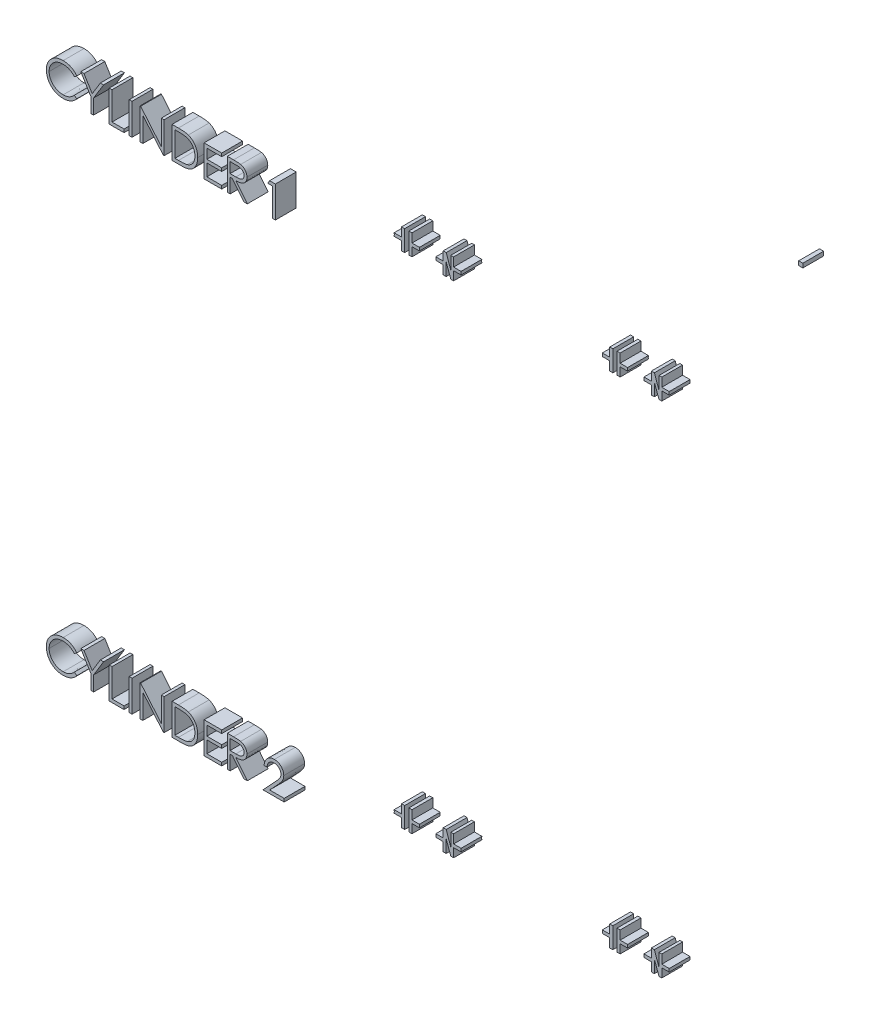
SolidWorks part; units mm, degrees
ref_plane "Front Plane" through (0, 0, 0) normal (0, 0, 1) x (1, 0, 0)
ref_plane "Top Plane" through (0, 0, 0) normal (0, 1, 0) x (1, 0, 0)
ref_plane "Right Plane" through (0, 0, 0) normal (1, 0, 0) x (0, 0, -1)
sketch "Sketch1" plane through (0, 0, 0) normal (0, 0, 1) x (1, 0, 0)
  line L0 (575.6423, 223.6264) -> (574.4644, 224.5188) construction
  line L1 (574.4644, 232.2112) -> (575.6423, 233.1126) construction
  line L2 (577.5654, 235.865) -> (582.3731, 227.9954) construction
  line L3 (582.3731, 227.9954) -> (582.3731, 220.865) construction
  line L4 (582.3731, 220.865) -> (583.7192, 220.865) construction
  line L5 (583.7192, 220.865) -> (583.7192, 227.9954) construction
  line L6 (583.7192, 227.9954) -> (588.5269, 235.865) construction
  line L7 (588.5269, 235.865) -> (586.9825, 235.865) construction
  line L8 (586.9825, 235.865) -> (583.0431, 229.4257) construction
  line L9 (583.0431, 229.4257) -> (579.1069, 235.865) construction
  line L10 (579.1069, 235.865) -> (577.5654, 235.865) construction
  line L11 (591.2192, 235.865) -> (591.2192, 220.865) construction
  line L12 (591.2192, 220.865) -> (598.3346, 220.865) construction
  line L13 (598.3346, 220.865) -> (598.3346, 222.4035) construction
  line L14 (598.3346, 222.4035) -> (592.5654, 222.4035) construction
  line L15 (592.5654, 222.4035) -> (592.5654, 235.865) construction
  line L16 (592.5654, 235.865) -> (591.2192, 235.865) construction
  line L17 (600.8346, 235.865) -> (600.8346, 220.865) construction
  line L18 (600.8346, 220.865) -> (602.1808, 220.865) construction
  line L19 (602.1808, 220.865) -> (602.1808, 235.865) construction
  line L20 (602.1808, 235.865) -> (600.8346, 235.865) construction
  line L21 (606.0269, 220.865) -> (607.3731, 220.865) construction
  line L22 (607.3731, 220.865) -> (607.3731, 232.6438) construction
  line L23 (607.3731, 232.6438) -> (617.2589, 220.865) construction
  line L24 (617.2589, 220.865) -> (617.5654, 220.865) construction
  line L25 (617.5654, 220.865) -> (617.5654, 235.865) construction
  line L26 (617.5654, 235.865) -> (616.2192, 235.865) construction
  line L27 (616.2192, 235.865) -> (616.2192, 224.0591) construction
  line L28 (616.2192, 224.0591) -> (606.3094, 235.865) construction
  line L29 (606.3094, 235.865) -> (606.0269, 235.865) construction
  line L30 (606.0269, 235.865) -> (606.0269, 220.865) construction
  line L31 (621.4115, 220.865) -> (626.06, 220.865) construction
  line L32 (624.4404, 235.865) -> (621.4115, 235.865) construction
  line L33 (621.4115, 235.865) -> (621.4115, 220.865) construction
  line L34 (636.7962, 235.865) -> (636.7962, 220.865) construction
  line L35 (636.7962, 220.865) -> (645.2577, 220.865) construction
  line L36 (645.2577, 220.865) -> (645.2577, 222.4035) construction
  line L37 (645.2577, 222.4035) -> (638.1423, 222.4035) construction
  line L38 (638.1423, 222.4035) -> (638.1423, 228.1727) construction
  line L39 (638.1423, 228.1727) -> (645.2577, 228.1727) construction
  line L40 (645.2577, 228.1727) -> (645.2577, 229.7112) construction
  line L41 (645.2577, 229.7112) -> (638.1423, 229.7112) construction
  line L42 (638.1423, 229.7112) -> (638.1423, 234.3265) construction
  line L43 (638.1423, 234.3265) -> (645.2577, 234.3265) construction
  line L44 (645.2577, 234.3265) -> (645.2577, 235.865) construction
  line L45 (645.2577, 235.865) -> (636.7962, 235.865) construction
  line L46 (647.95, 235.865) -> (647.95, 220.865) construction
  line L47 (647.95, 220.865) -> (649.2962, 220.865) construction
  line L48 (649.2962, 220.865) -> (649.2962, 227.7881) construction
  line L49 (649.2962, 227.7881) -> (650.3899, 227.7881) construction
  line L50 (650.3899, 227.7881) -> (655.9007, 220.865) construction
  line L51 (655.9007, 220.865) -> (657.5654, 220.865) construction
  line L52 (657.5654, 220.865) -> (652.0546, 227.7881) construction
  line L53 (650.9518, 235.865) -> (647.95, 235.865) construction
  line L54 (670.8827, 227.0729) -> (665.0654, 220.865) construction
  line L55 (665.0654, 220.865) -> (675.2577, 220.865) construction
  line L56 (675.2577, 220.865) -> (675.2577, 222.4035) construction
  line L57 (675.2577, 222.4035) -> (668.2805, 222.4035) construction
  line L58 (668.2805, 222.4035) -> (672.0335, 226.4059) construction
  line L59 (665.6423, 231.2496) -> (666.9885, 231.2496) construction
  line L60 (731.65, 242.615) -> (731.65, 238.365) construction
  line L61 (731.65, 238.365) -> (733.15, 238.365) construction
  line L62 (733.15, 238.365) -> (733.15, 248.365) construction
  line L63 (733.15, 248.365) -> (731.65, 248.365) construction
  line L64 (731.65, 248.365) -> (731.65, 244.115) construction
  line L65 (731.65, 244.115) -> (728.0791, 244.115) construction
  line L66 (728.0791, 242.615) -> (731.65, 242.615) construction
  line L67 (735.15, 238.365) -> (736.65, 238.365) construction
  line L68 (736.65, 238.365) -> (736.65, 242.615) construction
  line L69 (736.65, 242.615) -> (740.2209, 242.615) construction
  line L70 (740.2209, 244.115) -> (736.65, 244.115) construction
  line L71 (736.65, 244.115) -> (736.65, 248.365) construction
  line L72 (736.65, 248.365) -> (735.15, 248.365) construction
  line L73 (735.15, 248.365) -> (735.15, 238.365) construction
  line L74 (748.0791, 242.615) -> (751.65, 242.615) construction
  line L75 (751.65, 242.615) -> (751.65, 238.365) construction
  line L76 (751.65, 238.365) -> (753.0908, 238.365) construction
  line L77 (753.0908, 238.365) -> (753.0908, 244.4442) construction
  line L78 (753.0908, 244.4442) -> (755.3248, 238.365) construction
  line L79 (755.3248, 238.365) -> (756.65, 238.365) construction
  line L80 (756.65, 238.365) -> (756.65, 242.615) construction
  line L81 (756.65, 242.615) -> (760.2209, 242.615) construction
  line L82 (760.2209, 244.115) -> (756.65, 244.115) construction
  line L83 (756.65, 244.115) -> (756.65, 248.365) construction
  line L84 (756.65, 248.365) -> (755.3248, 248.365) construction
  line L85 (755.3248, 248.365) -> (755.3248, 242.0883) construction
  line L86 (755.3248, 242.0883) -> (753.0908, 248.365) construction
  line L87 (753.0908, 248.365) -> (751.65, 248.365) construction
  line L88 (751.65, 248.365) -> (751.65, 244.115) construction
  line L89 (751.65, 244.115) -> (748.0791, 244.115) construction
  line L90 (831.65, 242.615) -> (831.65, 238.365) construction
  line L91 (831.65, 238.365) -> (833.15, 238.365) construction
  line L92 (833.15, 238.365) -> (833.15, 248.365) construction
  line L93 (833.15, 248.365) -> (831.65, 248.365) construction
  line L94 (831.65, 248.365) -> (831.65, 244.115) construction
  line L95 (831.65, 244.115) -> (828.0791, 244.115) construction
  line L96 (828.0791, 242.615) -> (831.65, 242.615) construction
  line L97 (835.15, 238.365) -> (836.65, 238.365) construction
  line L98 (836.65, 238.365) -> (836.65, 242.615) construction
  line L99 (836.65, 242.615) -> (840.2209, 242.615) construction
  line L100 (840.2209, 244.115) -> (836.65, 244.115) construction
  line L101 (836.65, 244.115) -> (836.65, 248.365) construction
  line L102 (836.65, 248.365) -> (835.15, 248.365) construction
  line L103 (835.15, 248.365) -> (835.15, 238.365) construction
  line L104 (848.0791, 242.615) -> (851.65, 242.615) construction
  line L105 (851.65, 242.615) -> (851.65, 238.365) construction
  line L106 (851.65, 238.365) -> (853.0908, 238.365) construction
  line L107 (853.0908, 238.365) -> (853.0908, 244.4442) construction
  line L108 (853.0908, 244.4442) -> (855.3248, 238.365) construction
  line L109 (855.3248, 238.365) -> (856.65, 238.365) construction
  line L110 (856.65, 238.365) -> (856.65, 242.615) construction
  line L111 (856.65, 242.615) -> (860.2209, 242.615) construction
  line L112 (860.2209, 244.115) -> (856.65, 244.115) construction
  line L113 (856.65, 244.115) -> (856.65, 248.365) construction
  line L114 (856.65, 248.365) -> (855.3248, 248.365) construction
  line L115 (855.3248, 248.365) -> (855.3248, 242.0883) construction
  line L116 (855.3248, 242.0883) -> (853.0908, 248.365) construction
  line L117 (853.0908, 248.365) -> (851.65, 248.365) construction
  line L118 (851.65, 248.365) -> (851.65, 244.115) construction
  line L119 (851.65, 244.115) -> (848.0791, 244.115) construction
  line L120 (924.4, 567.6) -> (924.4, 569.6) construction
  line L121 (924.4, 569.6) -> (922.4, 569.6) construction
  line L122 (922.4, 569.6) -> (922.4, 567.6) construction
  line L123 (922.4, 567.6) -> (924.4, 567.6) construction
  line L124 (848.0791, 482.615) -> (851.65, 482.615) construction
  line L125 (851.65, 482.615) -> (851.65, 478.365) construction
  line L126 (851.65, 478.365) -> (853.0908, 478.365) construction
  line L127 (853.0908, 478.365) -> (853.0908, 484.4442) construction
  line L128 (853.0908, 484.4442) -> (855.3248, 478.365) construction
  line L129 (855.3248, 478.365) -> (856.65, 478.365) construction
  line L130 (856.65, 478.365) -> (856.65, 482.615) construction
  line L131 (856.65, 482.615) -> (860.2209, 482.615) construction
  line L132 (860.2209, 484.115) -> (856.65, 484.115) construction
  line L133 (856.65, 484.115) -> (856.65, 488.365) construction
  line L134 (856.65, 488.365) -> (855.3248, 488.365) construction
  line L135 (855.3248, 488.365) -> (855.3248, 482.0883) construction
  line L136 (855.3248, 482.0883) -> (853.0908, 488.365) construction
  line L137 (853.0908, 488.365) -> (851.65, 488.365) construction
  line L138 (851.65, 488.365) -> (851.65, 484.115) construction
  line L139 (851.65, 484.115) -> (848.0791, 484.115) construction
  line L140 (835.15, 478.365) -> (836.65, 478.365) construction
  line L141 (836.65, 478.365) -> (836.65, 482.615) construction
  line L142 (836.65, 482.615) -> (840.2209, 482.615) construction
  line L143 (840.2209, 484.115) -> (836.65, 484.115) construction
  line L144 (836.65, 484.115) -> (836.65, 488.365) construction
  line L145 (836.65, 488.365) -> (835.15, 488.365) construction
  line L146 (835.15, 488.365) -> (835.15, 478.365) construction
  line L147 (831.65, 482.615) -> (831.65, 478.365) construction
  line L148 (831.65, 478.365) -> (833.15, 478.365) construction
  line L149 (833.15, 478.365) -> (833.15, 488.365) construction
  line L150 (833.15, 488.365) -> (831.65, 488.365) construction
  line L151 (831.65, 488.365) -> (831.65, 484.115) construction
  line L152 (831.65, 484.115) -> (828.0791, 484.115) construction
  line L153 (828.0791, 482.615) -> (831.65, 482.615) construction
  line L154 (731.65, 482.615) -> (731.65, 478.365) construction
  line L155 (731.65, 478.365) -> (733.15, 478.365) construction
  line L156 (733.15, 478.365) -> (733.15, 488.365) construction
  line L157 (733.15, 488.365) -> (731.65, 488.365) construction
  line L158 (731.65, 488.365) -> (731.65, 484.115) construction
  line L159 (731.65, 484.115) -> (728.0791, 484.115) construction
  line L160 (728.0791, 482.615) -> (731.65, 482.615) construction
  line L161 (735.15, 478.365) -> (736.65, 478.365) construction
  line L162 (736.65, 478.365) -> (736.65, 482.615) construction
  line L163 (736.65, 482.615) -> (740.2209, 482.615) construction
  line L164 (740.2209, 484.115) -> (736.65, 484.115) construction
  line L165 (736.65, 484.115) -> (736.65, 488.365) construction
  line L166 (736.65, 488.365) -> (735.15, 488.365) construction
  line L167 (735.15, 488.365) -> (735.15, 478.365) construction
  line L168 (748.0791, 482.615) -> (751.65, 482.615) construction
  line L169 (751.65, 482.615) -> (751.65, 478.365) construction
  line L170 (751.65, 478.365) -> (753.0908, 478.365) construction
  line L171 (753.0908, 478.365) -> (753.0908, 484.4442) construction
  line L172 (753.0908, 484.4442) -> (755.3248, 478.365) construction
  line L173 (755.3248, 478.365) -> (756.65, 478.365) construction
  line L174 (756.65, 478.365) -> (756.65, 482.615) construction
  line L175 (756.65, 482.615) -> (760.2209, 482.615) construction
  line L176 (760.2209, 484.115) -> (756.65, 484.115) construction
  line L177 (756.65, 484.115) -> (756.65, 488.365) construction
  line L178 (756.65, 488.365) -> (755.3248, 488.365) construction
  line L179 (755.3248, 488.365) -> (755.3248, 482.0883) construction
  line L180 (755.3248, 482.0883) -> (753.0908, 488.365) construction
  line L181 (753.0908, 488.365) -> (751.65, 488.365) construction
  line L182 (751.65, 488.365) -> (751.65, 484.115) construction
  line L183 (751.65, 484.115) -> (748.0791, 484.115) construction
  line L184 (668.2535, 475.865) -> (667.3731, 474.3265) construction
  line L185 (667.3731, 474.3265) -> (669.6808, 474.3265) construction
  line L186 (669.6808, 474.3265) -> (669.6808, 460.865) construction
  line L187 (669.6808, 460.865) -> (671.0269, 460.865) construction
  line L188 (671.0269, 460.865) -> (671.0269, 475.865) construction
  line L189 (671.0269, 475.865) -> (668.2535, 475.865) construction
  line L190 (647.95, 475.865) -> (647.95, 460.865) construction
  line L191 (647.95, 460.865) -> (649.2962, 460.865) construction
  line L192 (649.2962, 460.865) -> (649.2962, 467.7881) construction
  line L193 (649.2962, 467.7881) -> (650.3899, 467.7881) construction
  line L194 (650.3899, 467.7881) -> (655.9007, 460.865) construction
  line L195 (655.9007, 460.865) -> (657.5654, 460.865) construction
  line L196 (657.5654, 460.865) -> (652.0546, 467.7881) construction
  line L197 (650.9518, 475.865) -> (647.95, 475.865) construction
  line L198 (636.7962, 475.865) -> (636.7962, 460.865) construction
  line L199 (636.7962, 460.865) -> (645.2577, 460.865) construction
  line L200 (645.2577, 460.865) -> (645.2577, 462.4035) construction
  line L201 (645.2577, 462.4035) -> (638.1423, 462.4035) construction
  line L202 (638.1423, 462.4035) -> (638.1423, 468.1727) construction
  line L203 (638.1423, 468.1727) -> (645.2577, 468.1727) construction
  line L204 (645.2577, 468.1727) -> (645.2577, 469.7112) construction
  line L205 (645.2577, 469.7112) -> (638.1423, 469.7112) construction
  line L206 (638.1423, 469.7112) -> (638.1423, 474.3265) construction
  line L207 (638.1423, 474.3265) -> (645.2577, 474.3265) construction
  line L208 (645.2577, 474.3265) -> (645.2577, 475.865) construction
  line L209 (645.2577, 475.865) -> (636.7962, 475.865) construction
  line L210 (621.4115, 460.865) -> (626.06, 460.865) construction
  line L211 (624.4404, 475.865) -> (621.4115, 475.865) construction
  line L212 (621.4115, 475.865) -> (621.4115, 460.865) construction
  line L213 (606.0269, 460.865) -> (607.3731, 460.865) construction
  line L214 (607.3731, 460.865) -> (607.3731, 472.6438) construction
  line L215 (607.3731, 472.6438) -> (617.2589, 460.865) construction
  line L216 (617.2589, 460.865) -> (617.5654, 460.865) construction
  line L217 (617.5654, 460.865) -> (617.5654, 475.865) construction
  line L218 (617.5654, 475.865) -> (616.2192, 475.865) construction
  line L219 (616.2192, 475.865) -> (616.2192, 464.0591) construction
  line L220 (616.2192, 464.0591) -> (606.3094, 475.865) construction
  line L221 (606.3094, 475.865) -> (606.0269, 475.865) construction
  line L222 (606.0269, 475.865) -> (606.0269, 460.865) construction
  line L223 (600.8346, 475.865) -> (600.8346, 460.865) construction
  line L224 (600.8346, 460.865) -> (602.1808, 460.865) construction
  line L225 (602.1808, 460.865) -> (602.1808, 475.865) construction
  line L226 (602.1808, 475.865) -> (600.8346, 475.865) construction
  line L227 (591.2192, 475.865) -> (591.2192, 460.865) construction
  line L228 (591.2192, 460.865) -> (598.3346, 460.865) construction
  line L229 (598.3346, 460.865) -> (598.3346, 462.4035) construction
  line L230 (598.3346, 462.4035) -> (592.5654, 462.4035) construction
  line L231 (592.5654, 462.4035) -> (592.5654, 475.865) construction
  line L232 (592.5654, 475.865) -> (591.2192, 475.865) construction
  line L233 (577.5654, 475.865) -> (582.3731, 467.9954) construction
  line L234 (582.3731, 467.9954) -> (582.3731, 460.865) construction
  line L235 (582.3731, 460.865) -> (583.7192, 460.865) construction
  line L236 (583.7192, 460.865) -> (583.7192, 467.9954) construction
  line L237 (583.7192, 467.9954) -> (588.5269, 475.865) construction
  line L238 (588.5269, 475.865) -> (586.9825, 475.865) construction
  line L239 (586.9825, 475.865) -> (583.0431, 469.4257) construction
  line L240 (583.0431, 469.4257) -> (579.1069, 475.865) construction
  line L241 (579.1069, 475.865) -> (577.5654, 475.865) construction
  line L242 (575.6423, 463.6264) -> (574.4644, 464.5188) construction
  line L243 (574.4644, 472.2112) -> (575.6423, 473.1126) construction
  line L244 (575.6423, 223.6264) -> (574.4644, 224.5188)
  line L245 (574.4644, 232.2112) -> (575.6423, 233.1126)
  line L246 (577.5654, 235.865) -> (582.3731, 227.9954)
  line L247 (582.3731, 227.9954) -> (582.3731, 220.865)
  line L248 (582.3731, 220.865) -> (583.7192, 220.865)
  line L249 (583.7192, 220.865) -> (583.7192, 227.9954)
  line L250 (583.7192, 227.9954) -> (588.5269, 235.865)
  line L251 (588.5269, 235.865) -> (586.9825, 235.865)
  line L252 (586.9825, 235.865) -> (583.0431, 229.4257)
  line L253 (583.0431, 229.4257) -> (579.1069, 235.865)
  line L254 (579.1069, 235.865) -> (577.5654, 235.865)
  line L255 (591.2192, 235.865) -> (591.2192, 220.865)
  line L256 (591.2192, 220.865) -> (598.3346, 220.865)
  line L257 (598.3346, 220.865) -> (598.3346, 222.4035)
  line L258 (598.3346, 222.4035) -> (592.5654, 222.4035)
  line L259 (592.5654, 222.4035) -> (592.5654, 235.865)
  line L260 (592.5654, 235.865) -> (591.2192, 235.865)
  line L261 (600.8346, 235.865) -> (600.8346, 220.865)
  line L262 (600.8346, 220.865) -> (602.1808, 220.865)
  line L263 (602.1808, 220.865) -> (602.1808, 235.865)
  line L264 (602.1808, 235.865) -> (600.8346, 235.865)
  line L265 (606.0269, 220.865) -> (607.3731, 220.865)
  line L266 (607.3731, 220.865) -> (607.3731, 232.6438)
  line L267 (607.3731, 232.6438) -> (617.2589, 220.865)
  line L268 (617.2589, 220.865) -> (617.5654, 220.865)
  line L269 (617.5654, 220.865) -> (617.5654, 235.865)
  line L270 (617.5654, 235.865) -> (616.2192, 235.865)
  line L271 (616.2192, 235.865) -> (616.2192, 224.0591)
  line L272 (616.2192, 224.0591) -> (606.3094, 235.865)
  line L273 (606.3094, 235.865) -> (606.0269, 235.865)
  line L274 (606.0269, 235.865) -> (606.0269, 220.865)
  line L275 (621.4115, 220.865) -> (626.06, 220.865)
  line L276 (624.4404, 235.865) -> (621.4115, 235.865)
  line L277 (621.4115, 235.865) -> (621.4115, 220.865)
  line L278 (636.7962, 235.865) -> (636.7962, 220.865)
  line L279 (636.7962, 220.865) -> (645.2577, 220.865)
  line L280 (645.2577, 220.865) -> (645.2577, 222.4035)
  line L281 (645.2577, 222.4035) -> (638.1423, 222.4035)
  line L282 (638.1423, 222.4035) -> (638.1423, 228.1727)
  line L283 (638.1423, 228.1727) -> (645.2577, 228.1727)
  line L284 (645.2577, 228.1727) -> (645.2577, 229.7112)
  line L285 (645.2577, 229.7112) -> (638.1423, 229.7112)
  line L286 (638.1423, 229.7112) -> (638.1423, 234.3265)
  line L287 (638.1423, 234.3265) -> (645.2577, 234.3265)
  line L288 (645.2577, 234.3265) -> (645.2577, 235.865)
  line L289 (645.2577, 235.865) -> (636.7962, 235.865)
  line L290 (647.95, 235.865) -> (647.95, 220.865)
  line L291 (647.95, 220.865) -> (649.2962, 220.865)
  line L292 (649.2962, 220.865) -> (649.2962, 227.7881)
  line L293 (649.2962, 227.7881) -> (650.3899, 227.7881)
  line L294 (650.3899, 227.7881) -> (655.9007, 220.865)
  line L295 (655.9007, 220.865) -> (657.5654, 220.865)
  line L296 (657.5654, 220.865) -> (652.0546, 227.7881)
  line L297 (650.9518, 235.865) -> (647.95, 235.865)
  line L298 (670.8827, 227.0729) -> (665.0654, 220.865)
  line L299 (665.0654, 220.865) -> (675.2577, 220.865)
  line L300 (675.2577, 220.865) -> (675.2577, 222.4035)
  line L301 (675.2577, 222.4035) -> (668.2805, 222.4035)
  line L302 (668.2805, 222.4035) -> (672.0335, 226.4059)
  line L303 (665.6423, 231.2496) -> (666.9885, 231.2496)
  line L304 (731.65, 242.615) -> (731.65, 238.365)
  line L305 (731.65, 238.365) -> (733.15, 238.365)
  line L306 (733.15, 238.365) -> (733.15, 248.365)
  line L307 (733.15, 248.365) -> (731.65, 248.365)
  line L308 (731.65, 248.365) -> (731.65, 244.115)
  line L309 (731.65, 244.115) -> (728.0791, 244.115)
  line L310 (728.0791, 242.615) -> (731.65, 242.615)
  line L311 (735.15, 238.365) -> (736.65, 238.365)
  line L312 (736.65, 238.365) -> (736.65, 242.615)
  line L313 (736.65, 242.615) -> (740.2209, 242.615)
  line L314 (740.2209, 244.115) -> (736.65, 244.115)
  line L315 (736.65, 244.115) -> (736.65, 248.365)
  line L316 (736.65, 248.365) -> (735.15, 248.365)
  line L317 (735.15, 248.365) -> (735.15, 238.365)
  line L318 (748.0791, 242.615) -> (751.65, 242.615)
  line L319 (751.65, 242.615) -> (751.65, 238.365)
  line L320 (751.65, 238.365) -> (753.0908, 238.365)
  line L321 (753.0908, 238.365) -> (753.0908, 244.4442)
  line L322 (753.0908, 244.4442) -> (755.3248, 238.365)
  line L323 (755.3248, 238.365) -> (756.65, 238.365)
  line L324 (756.65, 238.365) -> (756.65, 242.615)
  line L325 (756.65, 242.615) -> (760.2209, 242.615)
  line L326 (760.2209, 244.115) -> (756.65, 244.115)
  line L327 (756.65, 244.115) -> (756.65, 248.365)
  line L328 (756.65, 248.365) -> (755.3248, 248.365)
  line L329 (755.3248, 248.365) -> (755.3248, 242.0883)
  line L330 (755.3248, 242.0883) -> (753.0908, 248.365)
  line L331 (753.0908, 248.365) -> (751.65, 248.365)
  line L332 (751.65, 248.365) -> (751.65, 244.115)
  line L333 (751.65, 244.115) -> (748.0791, 244.115)
  line L334 (831.65, 242.615) -> (831.65, 238.365)
  line L335 (831.65, 238.365) -> (833.15, 238.365)
  line L336 (833.15, 238.365) -> (833.15, 248.365)
  line L337 (833.15, 248.365) -> (831.65, 248.365)
  line L338 (831.65, 248.365) -> (831.65, 244.115)
  line L339 (831.65, 244.115) -> (828.0791, 244.115)
  line L340 (828.0791, 242.615) -> (831.65, 242.615)
  line L341 (835.15, 238.365) -> (836.65, 238.365)
  line L342 (836.65, 238.365) -> (836.65, 242.615)
  line L343 (836.65, 242.615) -> (840.2209, 242.615)
  line L344 (840.2209, 244.115) -> (836.65, 244.115)
  line L345 (836.65, 244.115) -> (836.65, 248.365)
  line L346 (836.65, 248.365) -> (835.15, 248.365)
  line L347 (835.15, 248.365) -> (835.15, 238.365)
  line L348 (848.0791, 242.615) -> (851.65, 242.615)
  line L349 (851.65, 242.615) -> (851.65, 238.365)
  line L350 (851.65, 238.365) -> (853.0908, 238.365)
  line L351 (853.0908, 238.365) -> (853.0908, 244.4442)
  line L352 (853.0908, 244.4442) -> (855.3248, 238.365)
  line L353 (855.3248, 238.365) -> (856.65, 238.365)
  line L354 (856.65, 238.365) -> (856.65, 242.615)
  line L355 (856.65, 242.615) -> (860.2209, 242.615)
  line L356 (860.2209, 244.115) -> (856.65, 244.115)
  line L357 (856.65, 244.115) -> (856.65, 248.365)
  line L358 (856.65, 248.365) -> (855.3248, 248.365)
  line L359 (855.3248, 248.365) -> (855.3248, 242.0883)
  line L360 (855.3248, 242.0883) -> (853.0908, 248.365)
  line L361 (853.0908, 248.365) -> (851.65, 248.365)
  line L362 (851.65, 248.365) -> (851.65, 244.115)
  line L363 (851.65, 244.115) -> (848.0791, 244.115)
  line L364 (924.4, 567.6) -> (924.4, 569.6)
  line L365 (924.4, 569.6) -> (922.4, 569.6)
  line L366 (922.4, 569.6) -> (922.4, 567.6)
  line L367 (922.4, 567.6) -> (924.4, 567.6)
  line L368 (848.0791, 482.615) -> (851.65, 482.615)
  line L369 (851.65, 482.615) -> (851.65, 478.365)
  line L370 (851.65, 478.365) -> (853.0908, 478.365)
  line L371 (853.0908, 478.365) -> (853.0908, 484.4442)
  line L372 (853.0908, 484.4442) -> (855.3248, 478.365)
  line L373 (855.3248, 478.365) -> (856.65, 478.365)
  line L374 (856.65, 478.365) -> (856.65, 482.615)
  line L375 (856.65, 482.615) -> (860.2209, 482.615)
  line L376 (860.2209, 484.115) -> (856.65, 484.115)
  line L377 (856.65, 484.115) -> (856.65, 488.365)
  line L378 (856.65, 488.365) -> (855.3248, 488.365)
  line L379 (855.3248, 488.365) -> (855.3248, 482.0883)
  line L380 (855.3248, 482.0883) -> (853.0908, 488.365)
  line L381 (853.0908, 488.365) -> (851.65, 488.365)
  line L382 (851.65, 488.365) -> (851.65, 484.115)
  line L383 (851.65, 484.115) -> (848.0791, 484.115)
  line L384 (835.15, 478.365) -> (836.65, 478.365)
  line L385 (836.65, 478.365) -> (836.65, 482.615)
  line L386 (836.65, 482.615) -> (840.2209, 482.615)
  line L387 (840.2209, 484.115) -> (836.65, 484.115)
  line L388 (836.65, 484.115) -> (836.65, 488.365)
  line L389 (836.65, 488.365) -> (835.15, 488.365)
  line L390 (835.15, 488.365) -> (835.15, 478.365)
  line L391 (831.65, 482.615) -> (831.65, 478.365)
  line L392 (831.65, 478.365) -> (833.15, 478.365)
  line L393 (833.15, 478.365) -> (833.15, 488.365)
  line L394 (833.15, 488.365) -> (831.65, 488.365)
  line L395 (831.65, 488.365) -> (831.65, 484.115)
  line L396 (831.65, 484.115) -> (828.0791, 484.115)
  line L397 (828.0791, 482.615) -> (831.65, 482.615)
  line L398 (731.65, 482.615) -> (731.65, 478.365)
  line L399 (731.65, 478.365) -> (733.15, 478.365)
  line L400 (733.15, 478.365) -> (733.15, 488.365)
  line L401 (733.15, 488.365) -> (731.65, 488.365)
  line L402 (731.65, 488.365) -> (731.65, 484.115)
  line L403 (731.65, 484.115) -> (728.0791, 484.115)
  line L404 (728.0791, 482.615) -> (731.65, 482.615)
  line L405 (735.15, 478.365) -> (736.65, 478.365)
  line L406 (736.65, 478.365) -> (736.65, 482.615)
  line L407 (736.65, 482.615) -> (740.2209, 482.615)
  line L408 (740.2209, 484.115) -> (736.65, 484.115)
  line L409 (736.65, 484.115) -> (736.65, 488.365)
  line L410 (736.65, 488.365) -> (735.15, 488.365)
  line L411 (735.15, 488.365) -> (735.15, 478.365)
  line L412 (748.0791, 482.615) -> (751.65, 482.615)
  line L413 (751.65, 482.615) -> (751.65, 478.365)
  line L414 (751.65, 478.365) -> (753.0908, 478.365)
  line L415 (753.0908, 478.365) -> (753.0908, 484.4442)
  line L416 (753.0908, 484.4442) -> (755.3248, 478.365)
  line L417 (755.3248, 478.365) -> (756.65, 478.365)
  line L418 (756.65, 478.365) -> (756.65, 482.615)
  line L419 (756.65, 482.615) -> (760.2209, 482.615)
  line L420 (760.2209, 484.115) -> (756.65, 484.115)
  line L421 (756.65, 484.115) -> (756.65, 488.365)
  line L422 (756.65, 488.365) -> (755.3248, 488.365)
  line L423 (755.3248, 488.365) -> (755.3248, 482.0883)
  line L424 (755.3248, 482.0883) -> (753.0908, 488.365)
  line L425 (753.0908, 488.365) -> (751.65, 488.365)
  line L426 (751.65, 488.365) -> (751.65, 484.115)
  line L427 (751.65, 484.115) -> (748.0791, 484.115)
  line L428 (668.2535, 475.865) -> (667.3731, 474.3265)
  line L429 (667.3731, 474.3265) -> (669.6808, 474.3265)
  line L430 (669.6808, 474.3265) -> (669.6808, 460.865)
  line L431 (669.6808, 460.865) -> (671.0269, 460.865)
  line L432 (671.0269, 460.865) -> (671.0269, 475.865)
  line L433 (671.0269, 475.865) -> (668.2535, 475.865)
  line L434 (647.95, 475.865) -> (647.95, 460.865)
  line L435 (647.95, 460.865) -> (649.2962, 460.865)
  line L436 (649.2962, 460.865) -> (649.2962, 467.7881)
  line L437 (649.2962, 467.7881) -> (650.3899, 467.7881)
  line L438 (650.3899, 467.7881) -> (655.9007, 460.865)
  line L439 (655.9007, 460.865) -> (657.5654, 460.865)
  line L440 (657.5654, 460.865) -> (652.0546, 467.7881)
  line L441 (650.9518, 475.865) -> (647.95, 475.865)
  line L442 (636.7962, 475.865) -> (636.7962, 460.865)
  line L443 (636.7962, 460.865) -> (645.2577, 460.865)
  line L444 (645.2577, 460.865) -> (645.2577, 462.4035)
  line L445 (645.2577, 462.4035) -> (638.1423, 462.4035)
  line L446 (638.1423, 462.4035) -> (638.1423, 468.1727)
  line L447 (638.1423, 468.1727) -> (645.2577, 468.1727)
  line L448 (645.2577, 468.1727) -> (645.2577, 469.7112)
  line L449 (645.2577, 469.7112) -> (638.1423, 469.7112)
  line L450 (638.1423, 469.7112) -> (638.1423, 474.3265)
  line L451 (638.1423, 474.3265) -> (645.2577, 474.3265)
  line L452 (645.2577, 474.3265) -> (645.2577, 475.865)
  line L453 (645.2577, 475.865) -> (636.7962, 475.865)
  line L454 (621.4115, 460.865) -> (626.06, 460.865)
  line L455 (624.4404, 475.865) -> (621.4115, 475.865)
  line L456 (621.4115, 475.865) -> (621.4115, 460.865)
  line L457 (606.0269, 460.865) -> (607.3731, 460.865)
  line L458 (607.3731, 460.865) -> (607.3731, 472.6438)
  line L459 (607.3731, 472.6438) -> (617.2589, 460.865)
  line L460 (617.2589, 460.865) -> (617.5654, 460.865)
  line L461 (617.5654, 460.865) -> (617.5654, 475.865)
  line L462 (617.5654, 475.865) -> (616.2192, 475.865)
  line L463 (616.2192, 475.865) -> (616.2192, 464.0591)
  line L464 (616.2192, 464.0591) -> (606.3094, 475.865)
  line L465 (606.3094, 475.865) -> (606.0269, 475.865)
  line L466 (606.0269, 475.865) -> (606.0269, 460.865)
  line L467 (600.8346, 475.865) -> (600.8346, 460.865)
  line L468 (600.8346, 460.865) -> (602.1808, 460.865)
  line L469 (602.1808, 460.865) -> (602.1808, 475.865)
  line L470 (602.1808, 475.865) -> (600.8346, 475.865)
  line L471 (591.2192, 475.865) -> (591.2192, 460.865)
  line L472 (591.2192, 460.865) -> (598.3346, 460.865)
  line L473 (598.3346, 460.865) -> (598.3346, 462.4035)
  line L474 (598.3346, 462.4035) -> (592.5654, 462.4035)
  line L475 (592.5654, 462.4035) -> (592.5654, 475.865)
  line L476 (592.5654, 475.865) -> (591.2192, 475.865)
  line L477 (577.5654, 475.865) -> (582.3731, 467.9954)
  line L478 (582.3731, 467.9954) -> (582.3731, 460.865)
  line L479 (582.3731, 460.865) -> (583.7192, 460.865)
  line L480 (583.7192, 460.865) -> (583.7192, 467.9954)
  line L481 (583.7192, 467.9954) -> (588.5269, 475.865)
  line L482 (588.5269, 475.865) -> (586.9825, 475.865)
  line L483 (586.9825, 475.865) -> (583.0431, 469.4257)
  line L484 (583.0431, 469.4257) -> (579.1069, 475.865)
  line L485 (579.1069, 475.865) -> (577.5654, 475.865)
  line L486 (575.6423, 463.6264) -> (574.4644, 464.5188)
  line L487 (574.4644, 472.2112) -> (575.6423, 473.1126)
  line L488 (649.2962, 229.3265) -> (652.0425, 229.3055) construction
  line L489 (652.1087, 234.3265) -> (649.2962, 234.3265) construction
  line L490 (649.2962, 234.3265) -> (649.2962, 229.3265) construction
  line L491 (622.7577, 222.4035) -> (624.4794, 222.4035) construction
  line L492 (622.7577, 234.3265) -> (622.7577, 222.4035) construction
  line L493 (623.8124, 234.3265) -> (622.7577, 234.3265) construction
  line L494 (649.2962, 474.3265) -> (649.2962, 469.3265) construction
  line L495 (649.2962, 469.3265) -> (652.0425, 469.3055) construction
  line L496 (652.1087, 474.3265) -> (649.2962, 474.3265) construction
  line L497 (622.7577, 462.4035) -> (624.4794, 462.4035) construction
  line L498 (622.7577, 474.3265) -> (622.7577, 462.4035) construction
  line L499 (623.8124, 474.3265) -> (622.7577, 474.3265) construction
  line L500 (649.2962, 229.3265) -> (652.0425, 229.3055)
  line L501 (652.1087, 234.3265) -> (649.2962, 234.3265)
  line L502 (649.2962, 234.3265) -> (649.2962, 229.3265)
  line L503 (622.7577, 222.4035) -> (624.4794, 222.4035)
  line L504 (622.7577, 234.3265) -> (622.7577, 222.4035)
  line L505 (623.8124, 234.3265) -> (622.7577, 234.3265)
  line L506 (649.2962, 474.3265) -> (649.2962, 469.3265)
  line L507 (649.2962, 469.3265) -> (652.0425, 469.3055)
  line L508 (652.1087, 474.3265) -> (649.2962, 474.3265)
  line L509 (622.7577, 462.4035) -> (624.4794, 462.4035)
  line L510 (622.7577, 474.3265) -> (622.7577, 462.4035)
  line L511 (623.8124, 474.3265) -> (622.7577, 474.3265)
  arc A0 (728.0791, 242.615) -> (728.0791, 244.115) centre (724.15, 243.365) ccw construction
  arc A1 (740.2209, 244.115) -> (740.2209, 242.615) centre (744.15, 243.365) ccw construction
  arc A2 (748.0791, 242.615) -> (748.0791, 244.115) centre (744.15, 243.365) ccw construction
  arc A3 (760.2209, 244.115) -> (760.2209, 242.615) centre (764.15, 243.365) ccw construction
  arc A4 (828.0791, 242.615) -> (828.0791, 244.115) centre (824.15, 243.365) ccw construction
  arc A5 (840.2209, 244.115) -> (840.2209, 242.615) centre (844.15, 243.365) ccw construction
  arc A6 (848.0791, 242.615) -> (848.0791, 244.115) centre (844.15, 243.365) ccw construction
  arc A7 (860.2209, 244.115) -> (860.2209, 242.615) centre (864.15, 243.365) ccw construction
  arc A8 (848.0791, 482.615) -> (848.0791, 484.115) centre (844.15, 483.365) ccw construction
  arc A9 (860.2209, 484.115) -> (860.2209, 482.615) centre (864.15, 483.365) ccw construction
  arc A10 (840.2209, 484.115) -> (840.2209, 482.615) centre (844.15, 483.365) ccw construction
  arc A11 (828.0791, 482.615) -> (828.0791, 484.115) centre (824.15, 483.365) ccw construction
  arc A12 (728.0791, 482.615) -> (728.0791, 484.115) centre (724.15, 483.365) ccw construction
  arc A13 (740.2209, 484.115) -> (740.2209, 482.615) centre (744.15, 483.365) ccw construction
  arc A14 (748.0791, 482.615) -> (748.0791, 484.115) centre (744.15, 483.365) ccw construction
  arc A15 (760.2209, 484.115) -> (760.2209, 482.615) centre (764.15, 483.365) ccw construction
  arc A16 (728.0791, 242.615) -> (728.0791, 244.115) centre (724.15, 243.365) ccw
  arc A17 (740.2209, 244.115) -> (740.2209, 242.615) centre (744.15, 243.365) ccw
  arc A18 (748.0791, 242.615) -> (748.0791, 244.115) centre (744.15, 243.365) ccw
  arc A19 (760.2209, 244.115) -> (760.2209, 242.615) centre (764.15, 243.365) ccw
  arc A20 (828.0791, 242.615) -> (828.0791, 244.115) centre (824.15, 243.365) ccw
  arc A21 (840.2209, 244.115) -> (840.2209, 242.615) centre (844.15, 243.365) ccw
  arc A22 (848.0791, 242.615) -> (848.0791, 244.115) centre (844.15, 243.365) ccw
  arc A23 (860.2209, 244.115) -> (860.2209, 242.615) centre (864.15, 243.365) ccw
  arc A24 (848.0791, 482.615) -> (848.0791, 484.115) centre (844.15, 483.365) ccw
  arc A25 (860.2209, 484.115) -> (860.2209, 482.615) centre (864.15, 483.365) ccw
  arc A26 (840.2209, 484.115) -> (840.2209, 482.615) centre (844.15, 483.365) ccw
  arc A27 (828.0791, 482.615) -> (828.0791, 484.115) centre (824.15, 483.365) ccw
  arc A28 (728.0791, 482.615) -> (728.0791, 484.115) centre (724.15, 483.365) ccw
  arc A29 (740.2209, 484.115) -> (740.2209, 482.615) centre (744.15, 483.365) ccw
  arc A30 (748.0791, 482.615) -> (748.0791, 484.115) centre (744.15, 483.365) ccw
  arc A31 (760.2209, 484.115) -> (760.2209, 482.615) centre (764.15, 483.365) ccw
  spline S0 degree 3 poles (2958.7828, 2055.0453) (563.3784, 190.8312) (583.8231, 223.6922) (575.0704, 233.819) (574.7491, 234.137) (574.4143, 234.4387) (574.0565, 234.7158) (573.6817, 234.9742) (573.2871, 235.2117) (572.8761, 235.428) (572.4486, 235.6207) (572.0067, 235.788) (571.5533, 235.9343) (571.0856, 236.0466) (570.6073, 236.1371) (570.116, 236.2036) (555.8295, 237.3327) (540.2479, 199.1756) (639.0729, 3235.1585) knots -5.138235 -5.138235 -5.138235 -5.138235 0.060488 0.120645 0.180372 0.240194 0.299808 0.36026 0.42121 0.482873 0.54493 0.607605 0.670733 0.734318 0.798785 0.864317 0.931452 6.495074 6.495074 6.495074 6.495074 only from (575.6423, 233.1126) to (569.0978, 236.2496) construction
  spline S1 degree 3 poles (421.5832, 3232.231) (605.0326, 185.4497) (584.5574, 238.3799) (567.4428, 236.1214) (566.6624, 235.9485) (565.9189, 235.7015) (565.2138, 235.38) (564.5419, 234.9955) (563.9105, 234.5335) (563.321, 234.0083) (562.7833, 233.434) (562.3133, 232.8189) (561.9146, 232.1725) (561.5919, 231.4905) (561.3373, 230.7782) (561.1581, 230.0318) (558.8608, 213.9679) (612.6844, 194.197) (-2434.072, 393.5864) knots -3.927881 -3.927881 -3.927881 -3.927881 0.067672 0.133185 0.196585 0.258754 0.320345 0.381783 0.443742 0.507257 0.57053 0.631765 0.692252 0.751986 0.812045 0.872986 0.935442 4.687748 4.687748 4.687748 4.687748 only from (569.0978, 236.2496) to (561.0269, 228.4521) construction
  spline S2 degree 3 poles (-2435.1356, 82.7242) (610.0217, 262.3532) (559.0941, 243.0725) (561.1372, 226.9479) (561.282, 226.2334) (561.491, 225.5476) (561.7583, 224.8901) (562.0889, 224.2624) (570.3506, 211.4027) (620.9756, 230.3212) (-1818.3062, -1601.014) knots -8.004724 -8.004724 -8.004724 -8.004724 0.132689 0.261042 0.386386 0.509266 0.63122 0.752844 0.875671 8.51911 8.51911 8.51911 8.51911 only from (561.0269, 228.4521) to (562.929, 223.1036) construction
  spline S3 degree 3 poles (-1647.8568, -1804.4346) (574.3147, 265.6902) (554.8154, 230.9452) (563.5172, 222.4862) (563.8328, 222.209) (564.1611, 221.952) (564.5048, 221.7186) (564.859, 221.5014) (565.227, 221.3052) (565.6086, 221.1315) (566.0028, 220.9776) (566.4097, 220.8467) (566.8279, 220.7298) (567.2613, 220.6427) (567.706, 220.5688) (568.1645, 220.5197) (581.6657, 219.4887) (596.5004, 257.3258) (493.6151, -2778.2303) knots -5.053621 -5.053621 -5.053621 -5.053621 0.061868 0.123052 0.183446 0.243244 0.303001 0.362802 0.422604 0.483004 0.54382 0.605246 0.667586 0.73122 0.796083 0.86225 0.930337 6.641402 6.641402 6.641402 6.641402 only from (562.929, 223.1036) to (569.1159, 220.4804) construction
  spline S4 degree 3 poles (656.566, -2777.9367) (540.9646, 258.4457) (556.3162, 219.3712) (570.1207, 220.5279) (570.6066, 220.5888) (571.0811, 220.68) (571.5425, 220.7968) (571.9918, 220.9387) (572.4289, 221.1035) (572.8521, 221.296) (573.2607, 221.513) (573.6545, 221.75) (574.0319, 222.0084) (574.3881, 222.2919) (574.7295, 222.5925) (575.0521, 222.9161) (583.8862, 232.8398) (563.2139, 266.6968) (2921.9144, -1645.3929) knots -5.319659 -5.319659 -5.319659 -5.319659 0.067899 0.133987 0.199215 0.263039 0.326471 0.388856 0.45078 0.512609 0.574054 0.635137 0.695721 0.756273 0.816525 0.876947 0.938326 6.109071 6.109071 6.109071 6.109071 only from (569.1159, 220.4804) to (575.6423, 223.6264) construction
  spline S5 degree 3 poles (2734.2423, -1857.1668) (557.4115, 284.1916) (585.5254, 233.9561) (573.3361, 223.4181) (572.7121, 222.9865) (572.0549, 222.6305) (571.3636, 222.3567) (570.64, 222.161) (555.4553, 219.7366) (536.0282, 274.9793) (758.4316, -2771.6706) knots -7.50817 -7.50817 -7.50817 -7.50817 0.132189 0.259091 0.382819 0.50406 0.625245 0.747051 0.871485 8.15377 8.15377 8.15377 8.15377 only from (574.4644, 224.5188) to (569.1069, 222.0188) construction
  spline S6 degree 3 poles (417.1645, -2773.7611) (600.7174, 271.2496) (582.6019, 220.1406) (567.7187, 222.123) (567.0655, 222.2626) (566.444, 222.4608) (565.8552, 222.7187) (565.2947, 223.0287) (564.7686, 223.4004) (564.2783, 223.8226) (563.8314, 224.2848) (563.4431, 224.7838) (563.1078, 225.3076) (562.8424, 225.8644) (562.6272, 226.4446) (562.4836, 227.0554) (560.4346, 240.881) (611.5727, 258.5547) (-2431.4646, 40.008) knots -4.150534 -4.150534 -4.150534 -4.150534 0.068959 0.135498 0.199771 0.262666 0.324516 0.386081 0.448275 0.51116 0.573674 0.634571 0.694424 0.753854 0.813274 0.87371 0.935677 4.86229 4.86229 4.86229 4.86229 only from (569.1069, 222.0188) to (562.3731, 228.35) construction
  spline S7 degree 3 poles (-2435.0044, 349.1998) (601.5579, 204.0737) (561.2169, 217.6473) (562.4232, 229.2209) (562.488, 229.6418) (562.582, 230.0512) (562.7007, 230.4504) (562.8507, 230.8366) (563.0201, 231.2141) (563.2225, 231.5764) (563.4484, 231.9249) (563.6935, 232.2585) (563.9626, 232.5729) (564.2547, 232.8671) (564.5679, 233.1442) (564.9023, 233.4029) (565.2582, 233.6443) (565.6344, 233.8655) (566.0271, 234.0614) (566.4265, 234.2386) (566.8384, 234.3819) (567.2566, 234.5018) (567.6839, 234.5966) (568.1198, 234.6605) (579.9393, 235.8703) (593.7408, 195.5414) (449.6839, 3232.1659) knots -3.272829 -3.272829 -3.272829 -3.272829 0.043076 0.085457 0.126681 0.167541 0.208224 0.248373 0.288616 0.329131 0.369595 0.41002 0.450117 0.490508 0.531182 0.572314 0.614075 0.656879 0.699847 0.74235 0.784597 0.827248 0.869537 0.912498 0.956045 4.340893 4.340893 4.340893 4.340893 only from (562.3731, 228.35) to (569.0137, 234.7112) construction
  spline S8 degree 3 poles (759.2989, 3228.3871) (535.171, 180.6687) (555.0715, 237.0397) (570.6097, 234.5655) (571.3631, 234.3687) (571.9616, 234.1341) (572.4191, 233.9093) (572.7499, 233.7238) (573.0665, 233.517) (573.374, 233.2966) (573.6651, 233.0513) (573.9449, 232.7896) (582.1641, 224.2398) (563.4795, 192.099) (2845.5132, 2192.1192) knots -7.199768 -7.199768 -7.199768 -7.199768 0.131817 0.259156 0.383852 0.507544 0.569027 0.63015 0.690705 0.751706 0.812879 0.874525 0.936837 6.540058 6.540058 6.540058 6.540058 only from (569.0137, 234.7112) to (574.4644, 232.2112) construction
  spline S9 degree 3 poles (672.5465, -2778.4545) (590.769, 259.3603) (609.6199, 219.7535) (627.3381, 220.9114) (627.9271, 220.9719) (628.4778, 221.0622) (628.9906, 221.1761) (629.4664, 221.3126) (629.9041, 221.4773) (630.3056, 221.672) (630.6784, 221.8951) (631.0335, 222.1401) (631.3691, 222.4165) (631.6863, 222.7189) (631.9871, 223.0499) (632.2675, 223.4089) (632.5303, 223.7971) (632.7752, 224.2089) (632.9983, 224.6435) (633.1896, 225.0993) (633.3566, 225.57) (633.4869, 226.06) (633.5942, 226.564) (633.6635, 227.0865) (634.9485, 241.5929) (594.4752, 257.8895) (3631.7771, 129.1525) knots -4.256164 -4.256164 -4.256164 -4.256164 0.055037 0.106928 0.156011 0.202185 0.245558 0.286533 0.325147 0.361673 0.397287 0.433066 0.468805 0.505262 0.541925 0.57988 0.618417 0.658386 0.69892 0.739756 0.781177 0.822976 0.865705 0.909193 0.953919 4.483686 4.483686 4.483686 4.483686 only from (626.06, 220.865) to (633.7192, 228.1757) construction
  spline S10 degree 3 poles (3631.6986, 328.9524) (591.1099, 196.5616) (635.1404, 213.9988) (633.6503, 229.43) (633.5595, 230.0288) (633.4264, 230.6039) (633.2576, 231.156) (633.0542, 231.6864) (632.8094, 232.1936) (632.5276, 232.6749) (632.2152, 233.1295) (631.874, 233.552) (631.4968, 233.9337) (631.0991, 234.2884) (630.6653, 234.6011) (630.2053, 234.8806) (618.4971, 240.7914) (588.4635, 203.3705) (1773.4388, 3008.2231) knots -4.929026 -4.929026 -4.929026 -4.929026 0.070764 0.139466 0.206349 0.271441 0.334996 0.397655 0.459593 0.521506 0.582395 0.642353 0.701298 0.760125 0.818845 0.878306 0.938455 5.1598 5.1598 5.1598 5.1598 only from (633.7192, 228.1757) to (629.2, 235.3241) construction
  spline S11 degree 3 poles (1506.857, 3103.8089) (640.1559, 192.7435) (639.8164, 232.8303) (628.3305, 235.5696) (627.8198, 235.6617) (627.2521, 235.7352) (626.6288, 235.7951) (625.9483, 235.8362) (599.7683, 236.6633) (573.3183, 205.195) (594.2089, 3235.0541) knots -7.063487 -7.063487 -7.063487 -7.063487 0.08712 0.18423 0.292169 0.410633 0.541156 0.682594 0.835711 16.874003 16.874003 16.874003 16.874003 only from (629.2, 235.3241) to (624.4404, 235.865) construction
  spline S12 degree 3 poles (688.6472, -2771.6488) (621.3219, 258.8441) (637.5176, 226.9768) (652.9626, 227.8178) (653.3817, 227.8565) (653.7749, 227.9095) (654.1415, 227.9796) (654.4829, 228.0579) (654.7959, 228.1592) (655.1762, 228.3031) (655.6066, 228.5279) (656.0689, 228.8521) (656.4646, 229.2395) (656.7938, 229.6805) (657.0523, 230.1698) (657.24, 230.6978) (659.5766, 242.2439) (604.5479, 259.075) (3646.5908, -19.6368) knots -5.924729 -5.924729 -5.924729 -5.924729 0.062052 0.120621 0.175789 0.228041 0.2771 0.323011 0.366127 0.406783 0.483311 0.556994 0.62881 0.700809 0.773286 0.846279 0.92122 5.398357 5.398357 5.398357 5.398357 only from (652.0546, 227.7881) to (657.3731, 231.8536) construction
  spline S13 degree 3 poles (3654.2634, 363.9269) (620.1862, 210.7411) (658.4566, 222.6516) (657.3273, 232.559) (657.2612, 232.8928) (657.1675, 233.211) (657.051, 233.5166) (656.9048, 233.8066) (656.7351, 234.0839) (656.5339, 234.3404) (656.3206, 234.5848) (656.0842, 234.8038) (655.8342, 235.003) (655.5696, 235.1812) (655.2877, 235.3353) (654.9898, 235.4665) (646.2526, 238.6356) (626.3884, 203.577) (1474.7923, 3121.1266) knots -5.460407 -5.460407 -5.460407 -5.460407 0.068359 0.134815 0.198683 0.261561 0.323202 0.38431 0.445928 0.507648 0.56935 0.630173 0.690547 0.750868 0.811255 0.872936 0.935783 6.08595 6.08595 6.08595 6.08595 only from (657.3731, 231.8536) to (654.3502, 235.6607) construction
  spline S14 degree 3 poles (1208.8877, 3183.802) (666.3048, 203.845) (662.7473, 234.5517) (653.7881, 235.755) (653.438, 235.7857) (653.0386, 235.8178) (652.5885, 235.8355) (652.0878, 235.8559) (622.6958, 236.2367) (593.559, 215.2376) (551.9832, 3233.4073) knots -7.681786 -7.681786 -7.681786 -7.681786 0.073628 0.162615 0.265302 0.382842 0.515178 0.661566 0.823742 26.375708 26.375708 26.375708 26.375708 only from (654.3502, 235.6607) to (650.9518, 235.865) construction
  spline S15 degree 3 poles (-2308.6437, 611.5428) (704.2202, 205.699) (665.0512, 221.6455) (667.1006, 232.0209) (667.1948, 232.3765) (667.318, 232.7088) (667.4698, 233.0168) (667.6437, 233.3032) (667.8428, 233.5673) (668.0693, 233.8041) (668.3152, 234.0169) (668.5769, 234.2045) (668.8549, 234.3618) (669.1486, 234.488) (669.4565, 234.5873) (669.7791, 234.66) (679.4573, 235.8646) (691.3705, 197.7994) (519.7744, 3230.7251) knots -5.591308 -5.591308 -5.591308 -5.591308 0.073648 0.143686 0.210962 0.275557 0.338064 0.399311 0.4594 0.51934 0.579024 0.637809 0.695959 0.754122 0.813113 0.873453 0.935561 6.1608 6.1608 6.1608 6.1608 only from (666.9885, 231.2496) to (670.465, 234.7112) construction
  spline S16 degree 3 poles (848.6651, 3229.3157) (650.2508, 197.2506) (661.9963, 235.8805) (671.1206, 234.6591) (671.4308, 234.5903) (671.7276, 234.491) (672.0115, 234.3644) (672.2817, 234.2099) (672.5371, 234.0251) (672.7788, 233.8165) (672.9989, 233.5887) (673.1892, 233.3457) (673.354, 233.0944) (673.4895, 232.8311) (673.5921, 232.5554) (673.6637, 232.2701) (674.9421, 224.2927) (634.7028, 213.042) (3665.5015, 451.2275) knots -5.369784 -5.369784 -5.369784 -5.369784 0.068027 0.133505 0.19695 0.26027 0.322741 0.384982 0.448465 0.513424 0.578224 0.640011 0.700094 0.760067 0.819012 0.877878 0.938035 5.701048 5.701048 5.701048 5.701048 only from (670.465, 234.7112) to (673.7192, 231.6703) construction
  spline S17 degree 3 poles (3659.6775, -55.6681) (624.1774, 256.1611) (675.756, 240.668) (673.5967, 230.7051) (673.4265, 230.24) (673.2285, 229.8593) (673.024, 229.5476) (672.8356, 229.2787) (672.6004, 228.9864) (672.3354, 228.658) (672.0268, 228.304) (671.6812, 227.9194) (654.425, 209.3254) (618.7603, 208.4504) (2793.9238, -1891.623) knots -5.225017 -5.225017 -5.225017 -5.225017 0.088014 0.174976 0.2638 0.355443 0.406413 0.465519 0.533076 0.609353 0.693899 0.787171 0.889197 14.421483 14.421483 14.421483 14.421483 only from (673.7192, 231.6703) to (670.8827, 227.0729) construction
  spline S18 degree 3 poles (2810.9681, -1876.1257) (618.4968, 203.7427) (654.5423, 207.128) (672.8491, 227.2917) (673.2048, 227.7052) (673.5243, 228.0931) (673.8097, 228.4553) (674.0568, 228.7932) (674.2633, 229.1099) (674.4974, 229.4913) (674.7291, 229.9669) (674.9202, 230.5579) (677.361, 242.5865) (622.1495, 260.325) (3662.5012, -39.814) knots -12.596555 -12.596555 -12.596555 -12.596555 0.099512 0.192043 0.27766 0.357387 0.429567 0.495678 0.555172 0.608281 0.707183 0.804365 0.901316 6.486482 6.486482 6.486482 6.486482 only from (672.0335, 226.4059) to (675.0654, 231.7905) construction
  spline S19 degree 3 poles (3670.9525, 385.9366) (634.7491, 207.6863) (676.48, 221.4499) (674.995, 232.662) (674.894, 233.0766) (674.7609, 233.4789) (674.5801, 233.8631) (674.3632, 234.2326) (674.1099, 234.5904) (673.8163, 234.9256) (673.4965, 235.2395) (673.1413, 235.5062) (672.7667, 235.7367) (672.3681, 235.9287) (671.9425, 236.0715) (671.4935, 236.1732) (659.9076, 237.7692) (645.3118, 192.8001) (840.2684, 3231.2628) knots -4.584862 -4.584862 -4.584862 -4.584862 0.06271 0.123347 0.183401 0.242828 0.302097 0.36242 0.423725 0.487032 0.550491 0.612709 0.674265 0.73617 0.799211 0.863483 0.930525 5.731061 5.731061 5.731061 5.731061 only from (675.0654, 231.7905) to (670.5341, 236.2496) construction
  spline S20 degree 3 poles (509.21, 3231.7103) (695.7278, 192.0621) (681.1779, 237.7971) (669.554, 236.171) (669.0916, 236.0587) (668.6482, 235.9072) (668.2278, 235.7054) (667.8256, 235.4641) (667.4429, 235.1784) (667.0882, 234.8476) (666.7616, 234.487) (666.4736, 234.097) (666.2305, 233.6813) (666.0277, 233.2414) (665.8645, 232.7791) (665.749, 232.2903) (663.7866, 219.8539) (708.7678, 203.1834) (-2324.2241, 475.2235) knots -4.319892 -4.319892 -4.319892 -4.319892 0.06445 0.126725 0.187421 0.247417 0.306749 0.366595 0.427749 0.490235 0.553031 0.614805 0.676505 0.738096 0.801021 0.864897 0.931209 5.639996 5.639996 5.639996 5.639996 only from (670.5341, 236.2496) to (665.6423, 231.2496) construction
  spline S21 degree 3 poles (688.6472, -2531.6488) (621.3219, 498.8441) (637.5176, 466.9768) (652.9626, 467.8178) (653.3817, 467.8565) (653.7749, 467.9095) (654.1415, 467.9796) (654.4829, 468.0579) (654.7959, 468.1592) (655.1762, 468.3031) (655.6066, 468.5279) (656.0689, 468.8521) (656.4646, 469.2395) (656.7938, 469.6805) (657.0523, 470.1698) (657.24, 470.6978) (659.5766, 482.2439) (604.5479, 499.075) (3646.5908, 220.3632) knots -5.924729 -5.924729 -5.924729 -5.924729 0.062052 0.120621 0.175789 0.228041 0.2771 0.323011 0.366127 0.406783 0.483311 0.556994 0.62881 0.700809 0.773286 0.846279 0.92122 5.398357 5.398357 5.398357 5.398357 only from (652.0546, 467.7881) to (657.3731, 471.8536) construction
  spline S22 degree 3 poles (3654.2634, 603.9269) (620.1862, 450.7411) (658.4566, 462.6516) (657.3273, 472.559) (657.2612, 472.8928) (657.1675, 473.211) (657.051, 473.5166) (656.9048, 473.8066) (656.7351, 474.0839) (656.5339, 474.3404) (656.3206, 474.5848) (656.0842, 474.8038) (655.8342, 475.003) (655.5696, 475.1812) (655.2877, 475.3353) (654.9898, 475.4665) (646.2526, 478.6356) (626.3884, 443.577) (1474.7923, 3361.1266) knots -5.460407 -5.460407 -5.460407 -5.460407 0.068359 0.134815 0.198683 0.261561 0.323202 0.38431 0.445928 0.507648 0.56935 0.630173 0.690547 0.750868 0.811255 0.872936 0.935783 6.08595 6.08595 6.08595 6.08595 only from (657.3731, 471.8536) to (654.3502, 475.6607) construction
  spline S23 degree 3 poles (1208.8877, 3423.802) (666.3048, 443.845) (662.7473, 474.5517) (653.7881, 475.755) (653.438, 475.7857) (653.0386, 475.8178) (652.5885, 475.8355) (652.0878, 475.8559) (622.6958, 476.2367) (593.559, 455.2376) (551.9832, 3473.4073) knots -7.681786 -7.681786 -7.681786 -7.681786 0.073628 0.162615 0.265302 0.382842 0.515178 0.661566 0.823742 26.375708 26.375708 26.375708 26.375708 only from (654.3502, 475.6607) to (650.9518, 475.865) construction
  spline S24 degree 3 poles (672.5465, -2538.4545) (590.769, 499.3603) (609.6199, 459.7535) (627.3381, 460.9114) (627.9271, 460.9719) (628.4778, 461.0622) (628.9906, 461.1761) (629.4664, 461.3126) (629.9041, 461.4773) (630.3056, 461.672) (630.6784, 461.8951) (631.0335, 462.1401) (631.3691, 462.4165) (631.6863, 462.7189) (631.9871, 463.0499) (632.2675, 463.4089) (632.5303, 463.7971) (632.7752, 464.2089) (632.9983, 464.6435) (633.1896, 465.0993) (633.3566, 465.57) (633.4869, 466.06) (633.5942, 466.564) (633.6635, 467.0865) (634.9485, 481.5929) (594.4752, 497.8895) (3631.7771, 369.1525) knots -4.256164 -4.256164 -4.256164 -4.256164 0.055037 0.106928 0.156011 0.202185 0.245558 0.286533 0.325147 0.361673 0.397287 0.433066 0.468805 0.505262 0.541925 0.57988 0.618417 0.658386 0.69892 0.739756 0.781177 0.822976 0.865705 0.909193 0.953919 4.483686 4.483686 4.483686 4.483686 only from (626.06, 460.865) to (633.7192, 468.1757) construction
  spline S25 degree 3 poles (3631.6986, 568.9524) (591.1099, 436.5616) (635.1404, 453.9988) (633.6503, 469.43) (633.5595, 470.0288) (633.4264, 470.6039) (633.2576, 471.156) (633.0542, 471.6864) (632.8094, 472.1936) (632.5276, 472.6749) (632.2152, 473.1295) (631.874, 473.552) (631.4968, 473.9337) (631.0991, 474.2884) (630.6653, 474.6011) (630.2053, 474.8806) (618.4971, 480.7914) (588.4635, 443.3705) (1773.4388, 3248.2231) knots -4.929026 -4.929026 -4.929026 -4.929026 0.070764 0.139466 0.206349 0.271441 0.334996 0.397655 0.459593 0.521506 0.582395 0.642353 0.701298 0.760125 0.818845 0.878306 0.938455 5.1598 5.1598 5.1598 5.1598 only from (633.7192, 468.1757) to (629.2, 475.3241) construction
  spline S26 degree 3 poles (1506.857, 3343.8089) (640.1559, 432.7435) (639.8164, 472.8303) (628.3305, 475.5696) (627.8198, 475.6617) (627.2521, 475.7352) (626.6288, 475.7951) (625.9483, 475.8362) (599.7683, 476.6633) (573.3183, 445.195) (594.2089, 3475.0541) knots -7.063487 -7.063487 -7.063487 -7.063487 0.08712 0.18423 0.292169 0.410633 0.541156 0.682594 0.835711 16.874003 16.874003 16.874003 16.874003 only from (629.2, 475.3241) to (624.4404, 475.865) construction
  spline S27 degree 3 poles (2958.7828, 2295.0453) (563.3784, 430.8312) (583.8231, 463.6922) (575.0704, 473.819) (574.7491, 474.137) (574.4143, 474.4387) (574.0565, 474.7158) (573.6817, 474.9742) (573.2871, 475.2117) (572.8761, 475.428) (572.4486, 475.6207) (572.0067, 475.788) (571.5533, 475.9343) (571.0856, 476.0466) (570.6073, 476.1371) (570.116, 476.2036) (555.8295, 477.3327) (540.2479, 439.1756) (639.0729, 3475.1585) knots -5.138235 -5.138235 -5.138235 -5.138235 0.060488 0.120645 0.180372 0.240194 0.299808 0.36026 0.42121 0.482873 0.54493 0.607605 0.670733 0.734318 0.798785 0.864317 0.931452 6.495074 6.495074 6.495074 6.495074 only from (575.6423, 473.1126) to (569.0978, 476.2496) construction
  spline S28 degree 3 poles (421.5832, 3472.231) (605.0326, 425.4497) (584.5574, 478.3799) (567.4428, 476.1214) (566.6624, 475.9485) (565.9189, 475.7015) (565.2138, 475.38) (564.5419, 474.9955) (563.9105, 474.5335) (563.321, 474.0083) (562.7833, 473.434) (562.3133, 472.8189) (561.9146, 472.1725) (561.5919, 471.4905) (561.3373, 470.7782) (561.1581, 470.0318) (558.8608, 453.9679) (612.6844, 434.197) (-2434.072, 633.5864) knots -3.927881 -3.927881 -3.927881 -3.927881 0.067672 0.133185 0.196585 0.258754 0.320345 0.381783 0.443742 0.507257 0.57053 0.631765 0.692252 0.751986 0.812045 0.872986 0.935442 4.687748 4.687748 4.687748 4.687748 only from (569.0978, 476.2496) to (561.0269, 468.4521) construction
  spline S29 degree 3 poles (-2435.1356, 322.7242) (610.0217, 502.3532) (559.0941, 483.0725) (561.1372, 466.9479) (561.282, 466.2334) (561.491, 465.5476) (561.7583, 464.8901) (562.0889, 464.2624) (570.3506, 451.4027) (620.9756, 470.3212) (-1818.3062, -1361.014) knots -8.004724 -8.004724 -8.004724 -8.004724 0.132689 0.261042 0.386386 0.509266 0.63122 0.752844 0.875671 8.51911 8.51911 8.51911 8.51911 only from (561.0269, 468.4521) to (562.929, 463.1036) construction
  spline S30 degree 3 poles (-1647.8568, -1564.4346) (574.3147, 505.6902) (554.8154, 470.9452) (563.5172, 462.4862) (563.8328, 462.209) (564.1611, 461.952) (564.5048, 461.7186) (564.859, 461.5014) (565.227, 461.3052) (565.6086, 461.1315) (566.0028, 460.9776) (566.4097, 460.8467) (566.8279, 460.7298) (567.2613, 460.6427) (567.706, 460.5688) (568.1645, 460.5197) (581.6657, 459.4887) (596.5004, 497.3258) (493.6151, -2538.2303) knots -5.053621 -5.053621 -5.053621 -5.053621 0.061868 0.123052 0.183446 0.243244 0.303001 0.362802 0.422604 0.483004 0.54382 0.605246 0.667586 0.73122 0.796083 0.86225 0.930337 6.641402 6.641402 6.641402 6.641402 only from (562.929, 463.1036) to (569.1159, 460.4804) construction
  spline S31 degree 3 poles (656.566, -2537.9367) (540.9646, 498.4457) (556.3162, 459.3712) (570.1207, 460.5279) (570.6066, 460.5888) (571.0811, 460.68) (571.5425, 460.7968) (571.9918, 460.9387) (572.4289, 461.1035) (572.8521, 461.296) (573.2607, 461.513) (573.6545, 461.75) (574.0319, 462.0084) (574.3881, 462.2919) (574.7295, 462.5925) (575.0521, 462.9161) (583.8862, 472.8398) (563.2139, 506.6968) (2921.9144, -1405.3929) knots -5.319659 -5.319659 -5.319659 -5.319659 0.067899 0.133987 0.199215 0.263039 0.326471 0.388856 0.45078 0.512609 0.574054 0.635137 0.695721 0.756273 0.816525 0.876947 0.938326 6.109071 6.109071 6.109071 6.109071 only from (569.1159, 460.4804) to (575.6423, 463.6264) construction
  spline S32 degree 3 poles (2734.2423, -1617.1668) (557.4115, 524.1916) (585.5254, 473.9561) (573.3361, 463.4181) (572.7121, 462.9865) (572.0549, 462.6305) (571.3636, 462.3567) (570.64, 462.161) (555.4553, 459.7366) (536.0282, 514.9793) (758.4316, -2531.6706) knots -7.50817 -7.50817 -7.50817 -7.50817 0.132189 0.259091 0.382819 0.50406 0.625245 0.747051 0.871485 8.15377 8.15377 8.15377 8.15377 only from (574.4644, 464.5188) to (569.1069, 462.0188) construction
  spline S33 degree 3 poles (417.1645, -2533.7611) (600.7174, 511.2496) (582.6019, 460.1406) (567.7187, 462.123) (567.0655, 462.2626) (566.444, 462.4608) (565.8552, 462.7187) (565.2947, 463.0287) (564.7686, 463.4004) (564.2783, 463.8226) (563.8314, 464.2848) (563.4431, 464.7838) (563.1078, 465.3076) (562.8424, 465.8644) (562.6272, 466.4446) (562.4836, 467.0554) (560.4346, 480.881) (611.5727, 498.5547) (-2431.4646, 280.008) knots -4.150534 -4.150534 -4.150534 -4.150534 0.068959 0.135498 0.199771 0.262666 0.324516 0.386081 0.448275 0.51116 0.573674 0.634571 0.694424 0.753854 0.813274 0.87371 0.935677 4.86229 4.86229 4.86229 4.86229 only from (569.1069, 462.0188) to (562.3731, 468.35) construction
  spline S34 degree 3 poles (-2435.0044, 589.1998) (601.5579, 444.0737) (561.2169, 457.6473) (562.4232, 469.2209) (562.488, 469.6418) (562.582, 470.0512) (562.7007, 470.4504) (562.8507, 470.8366) (563.0201, 471.2141) (563.2225, 471.5764) (563.4484, 471.9249) (563.6935, 472.2585) (563.9626, 472.5729) (564.2547, 472.8671) (564.5679, 473.1442) (564.9023, 473.4029) (565.2582, 473.6443) (565.6344, 473.8655) (566.0271, 474.0614) (566.4265, 474.2386) (566.8384, 474.3819) (567.2566, 474.5018) (567.6839, 474.5966) (568.1198, 474.6605) (579.9393, 475.8703) (593.7408, 435.5414) (449.6839, 3472.1659) knots -3.272829 -3.272829 -3.272829 -3.272829 0.043076 0.085457 0.126681 0.167541 0.208224 0.248373 0.288616 0.329131 0.369595 0.41002 0.450117 0.490508 0.531182 0.572314 0.614075 0.656879 0.699847 0.74235 0.784597 0.827248 0.869537 0.912498 0.956045 4.340893 4.340893 4.340893 4.340893 only from (562.3731, 468.35) to (569.0137, 474.7112) construction
  spline S35 degree 3 poles (759.2989, 3468.3871) (535.171, 420.6687) (555.0715, 477.0397) (570.6097, 474.5655) (571.3631, 474.3687) (571.9616, 474.1341) (572.4191, 473.9093) (572.7499, 473.7238) (573.0665, 473.517) (573.374, 473.2966) (573.6651, 473.0513) (573.9449, 472.7896) (582.1641, 464.2398) (563.4795, 432.099) (2845.5132, 2432.1192) knots -7.199768 -7.199768 -7.199768 -7.199768 0.131817 0.259156 0.383852 0.507544 0.569027 0.63015 0.690705 0.751706 0.812879 0.874525 0.936837 6.540058 6.540058 6.540058 6.540058 only from (569.0137, 474.7112) to (574.4644, 472.2112) construction
  spline S36 degree 3 poles (575.6423, 233.1126) (575.5504, 233.2338) (575.3672, 233.4755) (575.0704, 233.819) (574.7491, 234.137) (574.4143, 234.4387) (574.0565, 234.7158) (573.6817, 234.9742) (573.2871, 235.2117) (572.8761, 235.428) (572.4486, 235.6207) (572.0067, 235.788) (571.5533, 235.9343) (571.0856, 236.0466) (570.6073, 236.1371) (570.116, 236.2036) (569.6113, 236.2435) (569.2702, 236.2475) (569.0978, 236.2496) knots 0 0 0 0 0.060488 0.120645 0.180372 0.240194 0.299808 0.36026 0.42121 0.482873 0.54493 0.607605 0.670733 0.734318 0.798785 0.864317 0.931452 1 1 1 1
  spline S37 degree 3 poles (569.0978, 236.2496) (568.815, 236.2427) (568.2585, 236.2291) (567.4428, 236.1214) (566.6624, 235.9485) (565.9189, 235.7015) (565.2138, 235.38) (564.5419, 234.9955) (563.9105, 234.5335) (563.321, 234.0083) (562.7833, 233.434) (562.3133, 232.8189) (561.9146, 232.1725) (561.5919, 231.4905) (561.3373, 230.7782) (561.1581, 230.0318) (561.0467, 229.2528) (561.0336, 228.7219) (561.0269, 228.4521) knots 0 0 0 0 0.067672 0.133185 0.196585 0.258754 0.320345 0.381783 0.443742 0.507257 0.57053 0.631765 0.692252 0.751986 0.812045 0.872986 0.935442 1 1 1 1
  spline S38 degree 3 poles (561.0269, 228.4521) (561.0324, 228.1954) (561.0432, 227.6904) (561.1372, 226.9479) (561.282, 226.2334) (561.491, 225.5476) (561.7583, 224.8901) (562.0889, 224.2624) (562.4752, 223.6611) (562.7771, 223.2902) (562.929, 223.1036) knots 0 0 0 0 0.132689 0.261042 0.386386 0.509266 0.63122 0.752844 0.875671 1 1 1 1
  spline S39 degree 3 poles (562.929, 223.1036) (563.0238, 222.9962) (563.2124, 222.7825) (563.5172, 222.4862) (563.8328, 222.209) (564.1611, 221.952) (564.5048, 221.7186) (564.859, 221.5014) (565.227, 221.3052) (565.6086, 221.1315) (566.0028, 220.9776) (566.4097, 220.8467) (566.8279, 220.7298) (567.2613, 220.6427) (567.706, 220.5688) (568.1645, 220.5197) (568.6355, 220.4837) (568.9545, 220.4815) (569.1159, 220.4804) knots 0 0 0 0 0.061868 0.123052 0.183446 0.243244 0.303001 0.362802 0.422604 0.483004 0.54382 0.605246 0.667586 0.73122 0.796083 0.86225 0.930337 1 1 1 1
  spline S40 degree 3 poles (569.1159, 220.4804) (569.2862, 220.4823) (569.6224, 220.4861) (570.1207, 220.5279) (570.6066, 220.5888) (571.0811, 220.68) (571.5425, 220.7968) (571.9918, 220.9387) (572.4289, 221.1035) (572.8521, 221.296) (573.2607, 221.513) (573.6545, 221.75) (574.0319, 222.0084) (574.3881, 222.2919) (574.7295, 222.5925) (575.0521, 222.9161) (575.3584, 223.2601) (575.5475, 223.5041) (575.6423, 223.6264) knots 0 0 0 0 0.067899 0.133987 0.199215 0.263039 0.326471 0.388856 0.45078 0.512609 0.574054 0.635137 0.695721 0.756273 0.816525 0.876947 0.938326 1 1 1 1
  spline S41 degree 3 poles (574.4644, 224.5188) (574.283, 224.3197) (573.9274, 223.9293) (573.3361, 223.4181) (572.7121, 222.9865) (572.0549, 222.6305) (571.3636, 222.3567) (570.64, 222.161) (569.8841, 222.0403) (569.3687, 222.0261) (569.1069, 222.0188) knots 0 0 0 0 0.132189 0.259091 0.382819 0.50406 0.625245 0.747051 0.871485 1 1 1 1
  spline S42 degree 3 poles (569.1069, 222.0188) (568.8692, 222.0233) (568.4022, 222.032) (567.7187, 222.123) (567.0655, 222.2626) (566.444, 222.4608) (565.8552, 222.7187) (565.2947, 223.0287) (564.7686, 223.4004) (564.2783, 223.8226) (563.8314, 224.2848) (563.4431, 224.7838) (563.1078, 225.3076) (562.8424, 225.8644) (562.6272, 226.4446) (562.4836, 227.0554) (562.3891, 227.693) (562.3785, 228.1283) (562.3731, 228.35) knots 0 0 0 0 0.068959 0.135498 0.199771 0.262666 0.324516 0.386081 0.448275 0.51116 0.573674 0.634571 0.694424 0.753854 0.813274 0.87371 0.935677 1 1 1 1
  spline S43 degree 3 poles (562.3731, 228.35) (562.3748, 228.4973) (562.3782, 228.7897) (562.4232, 229.2209) (562.488, 229.6418) (562.582, 230.0512) (562.7007, 230.4504) (562.8507, 230.8366) (563.0201, 231.2141) (563.2225, 231.5764) (563.4484, 231.9249) (563.6935, 232.2585) (563.9626, 232.5729) (564.2547, 232.8671) (564.5679, 233.1442) (564.9023, 233.4029) (565.2582, 233.6443) (565.6344, 233.8655) (566.0271, 234.0614) (566.4265, 234.2386) (566.8384, 234.3819) (567.2566, 234.5018) (567.6839, 234.5966) (568.1198, 234.6605) (568.564, 234.706) (568.8633, 234.7094) (569.0137, 234.7112) knots 0 0 0 0 0.043076 0.085457 0.126681 0.167541 0.208224 0.248373 0.288616 0.329131 0.369595 0.41002 0.450117 0.490508 0.531182 0.572314 0.614075 0.656879 0.699847 0.74235 0.784597 0.827248 0.869537 0.912498 0.956045 1 1 1 1
  spline S44 degree 3 poles (569.0137, 234.7112) (569.2866, 234.7043) (569.8232, 234.6907) (570.6097, 234.5655) (571.3631, 234.3687) (571.9616, 234.1341) (572.4191, 233.9093) (572.7499, 233.7238) (573.0665, 233.517) (573.374, 233.2966) (573.6651, 233.0513) (573.9449, 232.7896) (574.2135, 232.5102) (574.3804, 232.3113) (574.4644, 232.2112) knots 0 0 0 0 0.131817 0.259156 0.383852 0.507544 0.569027 0.63015 0.690705 0.751706 0.812879 0.874525 0.936837 1 1 1 1
  spline S45 degree 3 poles (626.06, 220.865) (626.2814, 220.8668) (626.7116, 220.8704) (627.3381, 220.9114) (627.9271, 220.9719) (628.4778, 221.0622) (628.9906, 221.1761) (629.4664, 221.3126) (629.9041, 221.4773) (630.3056, 221.672) (630.6784, 221.8951) (631.0335, 222.1401) (631.3691, 222.4165) (631.6863, 222.7189) (631.9871, 223.0499) (632.2675, 223.4089) (632.5303, 223.7971) (632.7752, 224.2089) (632.9983, 224.6435) (633.1896, 225.0993) (633.3566, 225.57) (633.4869, 226.06) (633.5942, 226.564) (633.6635, 227.0865) (633.7112, 227.6249) (633.7165, 227.9903) (633.7192, 228.1757) knots 0 0 0 0 0.055037 0.106928 0.156011 0.202185 0.245558 0.286533 0.325147 0.361673 0.397287 0.433066 0.468805 0.505262 0.541925 0.57988 0.618417 0.658386 0.69892 0.739756 0.781177 0.822976 0.865705 0.909193 0.953919 1 1 1 1
  spline S46 degree 3 poles (633.7192, 228.1757) (633.7162, 228.3892) (633.7102, 228.8099) (633.6503, 229.43) (633.5595, 230.0288) (633.4264, 230.6039) (633.2576, 231.156) (633.0542, 231.6864) (632.8094, 232.1936) (632.5276, 232.6749) (632.2152, 233.1295) (631.874, 233.552) (631.4968, 233.9337) (631.0991, 234.2884) (630.6653, 234.6011) (630.2053, 234.8806) (629.7167, 235.1272) (629.3735, 235.258) (629.2, 235.3241) knots 0 0 0 0 0.070764 0.139466 0.206349 0.271441 0.334996 0.397655 0.459593 0.521506 0.582395 0.642353 0.701298 0.760125 0.818845 0.878306 0.938455 1 1 1 1
  spline S47 degree 3 poles (629.2, 235.3241) (629.0673, 235.368) (628.7867, 235.4608) (628.3305, 235.5696) (627.8198, 235.6617) (627.2521, 235.7352) (626.6288, 235.7951) (625.9483, 235.8362) (625.2128, 235.8594) (624.7038, 235.8631) (624.4404, 235.865) knots 0 0 0 0 0.08712 0.18423 0.292169 0.410633 0.541156 0.682594 0.835711 1 1 1 1
  spline S48 degree 3 poles (652.0546, 227.7881) (652.2119, 227.7899) (652.5176, 227.7935) (652.9626, 227.8178) (653.3817, 227.8565) (653.7749, 227.9095) (654.1415, 227.9796) (654.4829, 228.0579) (654.7959, 228.1592) (655.1762, 228.3031) (655.6066, 228.5279) (656.0689, 228.8521) (656.4646, 229.2395) (656.7938, 229.6805) (657.0523, 230.1698) (657.24, 230.6978) (657.3545, 231.2637) (657.3668, 231.6537) (657.3731, 231.8536) knots 0 0 0 0 0.062052 0.120621 0.175789 0.228041 0.2771 0.323011 0.366127 0.406783 0.483311 0.556994 0.62881 0.700809 0.773286 0.846279 0.92122 1 1 1 1
  spline S49 degree 3 poles (657.3731, 231.8536) (657.371, 231.9739) (657.367, 232.2111) (657.3273, 232.559) (657.2612, 232.8928) (657.1675, 233.211) (657.051, 233.5166) (656.9048, 233.8066) (656.7351, 234.0839) (656.5339, 234.3404) (656.3206, 234.5848) (656.0842, 234.8038) (655.8342, 235.003) (655.5696, 235.1812) (655.2877, 235.3353) (654.9898, 235.4665) (654.6771, 235.5799) (654.46, 235.6336) (654.3502, 235.6607) knots 0 0 0 0 0.068359 0.134815 0.198683 0.261561 0.323202 0.38431 0.445928 0.507648 0.56935 0.630173 0.690547 0.750868 0.811255 0.872936 0.935783 1 1 1 1
  spline S50 degree 3 poles (654.3502, 235.6607) (654.2683, 235.6776) (654.0872, 235.7149) (653.7881, 235.755) (653.438, 235.7857) (653.0386, 235.8178) (652.5885, 235.8355) (652.0878, 235.8559) (651.5368, 235.8631) (651.1521, 235.8643) (650.9518, 235.865) knots 0 0 0 0 0.073628 0.162615 0.265302 0.382842 0.515178 0.661566 0.823742 1 1 1 1
  spline S51 degree 3 poles (666.9885, 231.2496) (667.0012, 231.3831) (667.0261, 231.6436) (667.1006, 232.0209) (667.1948, 232.3765) (667.318, 232.7088) (667.4698, 233.0168) (667.6437, 233.3032) (667.8428, 233.5673) (668.0693, 233.8041) (668.3152, 234.0169) (668.5769, 234.2045) (668.8549, 234.3618) (669.1486, 234.488) (669.4565, 234.5873) (669.7791, 234.66) (670.1174, 234.7021) (670.3477, 234.7081) (670.465, 234.7112) knots 0 0 0 0 0.073648 0.143686 0.210962 0.275557 0.338064 0.399311 0.4594 0.51934 0.579024 0.637809 0.695959 0.754122 0.813113 0.873453 0.935561 1 1 1 1
  spline S52 degree 3 poles (670.465, 234.7112) (670.5773, 234.7082) (670.7978, 234.7023) (671.1206, 234.6591) (671.4308, 234.5903) (671.7276, 234.491) (672.0115, 234.3644) (672.2817, 234.2099) (672.5371, 234.0251) (672.7788, 233.8165) (672.9989, 233.5887) (673.1892, 233.3457) (673.354, 233.0944) (673.4895, 232.8311) (673.5921, 232.5554) (673.6637, 232.2701) (673.7111, 231.9743) (673.7165, 231.7726) (673.7192, 231.6703) knots 0 0 0 0 0.068027 0.133505 0.19695 0.26027 0.322741 0.384982 0.448465 0.513424 0.578224 0.640011 0.700094 0.760067 0.819012 0.877878 0.938035 1 1 1 1
  spline S53 degree 3 poles (673.7192, 231.6703) (673.713, 231.5075) (673.7005, 231.1839) (673.5967, 230.7051) (673.4265, 230.24) (673.2285, 229.8593) (673.024, 229.5476) (672.8356, 229.2787) (672.6004, 228.9864) (672.3354, 228.658) (672.0268, 228.304) (671.6812, 227.9194) (671.2964, 227.5048) (671.0243, 227.2208) (670.8827, 227.0729) knots 0 0 0 0 0.088014 0.174976 0.2638 0.355443 0.406413 0.465519 0.533076 0.609353 0.693899 0.787171 0.889197 1 1 1 1
  spline S54 degree 3 poles (672.0335, 226.4059) (672.1771, 226.5598) (672.4542, 226.8568) (672.8491, 227.2917) (673.2048, 227.7052) (673.5243, 228.0931) (673.8097, 228.4553) (674.0568, 228.7932) (674.2633, 229.1099) (674.4974, 229.4913) (674.7291, 229.9669) (674.9202, 230.5579) (675.0438, 231.1674) (675.0582, 231.5816) (675.0654, 231.7905) knots 0 0 0 0 0.099512 0.192043 0.27766 0.357387 0.429567 0.495678 0.555172 0.608281 0.707183 0.804365 0.901316 1 1 1 1
  spline S55 degree 3 poles (675.0654, 231.7905) (675.0609, 231.9389) (675.0522, 232.2308) (674.995, 232.662) (674.894, 233.0766) (674.7609, 233.4789) (674.5801, 233.8631) (674.3632, 234.2326) (674.1099, 234.5904) (673.8163, 234.9256) (673.4965, 235.2395) (673.1413, 235.5062) (672.7667, 235.7367) (672.3681, 235.9287) (671.9425, 236.0715) (671.4935, 236.1732) (671.0218, 236.2382) (670.6986, 236.2458) (670.5341, 236.2496) knots 0 0 0 0 0.06271 0.123347 0.183401 0.242828 0.302097 0.36242 0.423725 0.487032 0.550491 0.612709 0.674265 0.73617 0.799211 0.863483 0.930525 1 1 1 1
  spline S56 degree 3 poles (670.5341, 236.2496) (670.3667, 236.2459) (670.0373, 236.2387) (669.554, 236.171) (669.0916, 236.0587) (668.6482, 235.9072) (668.2278, 235.7054) (667.8256, 235.4641) (667.4429, 235.1784) (667.0882, 234.8476) (666.7616, 234.487) (666.4736, 234.097) (666.2305, 233.6813) (666.0277, 233.2414) (665.8645, 232.7791) (665.749, 232.2903) (665.6683, 231.7789) (665.6511, 231.4282) (665.6423, 231.2496) knots 0 0 0 0 0.06445 0.126725 0.187421 0.247417 0.306749 0.366595 0.427749 0.490235 0.553031 0.614805 0.676505 0.738096 0.801021 0.864897 0.931209 1 1 1 1
  spline S57 degree 3 poles (652.0546, 467.7881) (652.2119, 467.7899) (652.5176, 467.7935) (652.9626, 467.8178) (653.3817, 467.8565) (653.7749, 467.9095) (654.1415, 467.9796) (654.4829, 468.0579) (654.7959, 468.1592) (655.1762, 468.3031) (655.6066, 468.5279) (656.0689, 468.8521) (656.4646, 469.2395) (656.7938, 469.6805) (657.0523, 470.1698) (657.24, 470.6978) (657.3545, 471.2637) (657.3668, 471.6537) (657.3731, 471.8536) knots 0 0 0 0 0.062052 0.120621 0.175789 0.228041 0.2771 0.323011 0.366127 0.406783 0.483311 0.556994 0.62881 0.700809 0.773286 0.846279 0.92122 1 1 1 1
  spline S58 degree 3 poles (657.3731, 471.8536) (657.371, 471.9739) (657.367, 472.2111) (657.3273, 472.559) (657.2612, 472.8928) (657.1675, 473.211) (657.051, 473.5166) (656.9048, 473.8066) (656.7351, 474.0839) (656.5339, 474.3404) (656.3206, 474.5848) (656.0842, 474.8038) (655.8342, 475.003) (655.5696, 475.1812) (655.2877, 475.3353) (654.9898, 475.4665) (654.6771, 475.5799) (654.46, 475.6336) (654.3502, 475.6607) knots 0 0 0 0 0.068359 0.134815 0.198683 0.261561 0.323202 0.38431 0.445928 0.507648 0.56935 0.630173 0.690547 0.750868 0.811255 0.872936 0.935783 1 1 1 1
  spline S59 degree 3 poles (654.3502, 475.6607) (654.2683, 475.6776) (654.0872, 475.7149) (653.7881, 475.755) (653.438, 475.7857) (653.0386, 475.8178) (652.5885, 475.8355) (652.0878, 475.8559) (651.5368, 475.8631) (651.1521, 475.8643) (650.9518, 475.865) knots 0 0 0 0 0.073628 0.162615 0.265302 0.382842 0.515178 0.661566 0.823742 1 1 1 1
  spline S60 degree 3 poles (626.06, 460.865) (626.2814, 460.8668) (626.7116, 460.8704) (627.3381, 460.9114) (627.9271, 460.9719) (628.4778, 461.0622) (628.9906, 461.1761) (629.4664, 461.3126) (629.9041, 461.4773) (630.3056, 461.672) (630.6784, 461.8951) (631.0335, 462.1401) (631.3691, 462.4165) (631.6863, 462.7189) (631.9871, 463.0499) (632.2675, 463.4089) (632.5303, 463.7971) (632.7752, 464.2089) (632.9983, 464.6435) (633.1896, 465.0993) (633.3566, 465.57) (633.4869, 466.06) (633.5942, 466.564) (633.6635, 467.0865) (633.7112, 467.6249) (633.7165, 467.9903) (633.7192, 468.1757) knots 0 0 0 0 0.055037 0.106928 0.156011 0.202185 0.245558 0.286533 0.325147 0.361673 0.397287 0.433066 0.468805 0.505262 0.541925 0.57988 0.618417 0.658386 0.69892 0.739756 0.781177 0.822976 0.865705 0.909193 0.953919 1 1 1 1
  spline S61 degree 3 poles (633.7192, 468.1757) (633.7162, 468.3892) (633.7102, 468.8099) (633.6503, 469.43) (633.5595, 470.0288) (633.4264, 470.6039) (633.2576, 471.156) (633.0542, 471.6864) (632.8094, 472.1936) (632.5276, 472.6749) (632.2152, 473.1295) (631.874, 473.552) (631.4968, 473.9337) (631.0991, 474.2884) (630.6653, 474.6011) (630.2053, 474.8806) (629.7167, 475.1272) (629.3735, 475.258) (629.2, 475.3241) knots 0 0 0 0 0.070764 0.139466 0.206349 0.271441 0.334996 0.397655 0.459593 0.521506 0.582395 0.642353 0.701298 0.760125 0.818845 0.878306 0.938455 1 1 1 1
  spline S62 degree 3 poles (629.2, 475.3241) (629.0673, 475.368) (628.7867, 475.4608) (628.3305, 475.5696) (627.8198, 475.6617) (627.2521, 475.7352) (626.6288, 475.7951) (625.9483, 475.8362) (625.2128, 475.8594) (624.7038, 475.8631) (624.4404, 475.865) knots 0 0 0 0 0.08712 0.18423 0.292169 0.410633 0.541156 0.682594 0.835711 1 1 1 1
  spline S63 degree 3 poles (575.6423, 473.1126) (575.5504, 473.2338) (575.3672, 473.4755) (575.0704, 473.819) (574.7491, 474.137) (574.4143, 474.4387) (574.0565, 474.7158) (573.6817, 474.9742) (573.2871, 475.2117) (572.8761, 475.428) (572.4486, 475.6207) (572.0067, 475.788) (571.5533, 475.9343) (571.0856, 476.0466) (570.6073, 476.1371) (570.116, 476.2036) (569.6113, 476.2435) (569.2702, 476.2475) (569.0978, 476.2496) knots 0 0 0 0 0.060488 0.120645 0.180372 0.240194 0.299808 0.36026 0.42121 0.482873 0.54493 0.607605 0.670733 0.734318 0.798785 0.864317 0.931452 1 1 1 1
  spline S64 degree 3 poles (569.0978, 476.2496) (568.815, 476.2427) (568.2585, 476.2291) (567.4428, 476.1214) (566.6624, 475.9485) (565.9189, 475.7015) (565.2138, 475.38) (564.5419, 474.9955) (563.9105, 474.5335) (563.321, 474.0083) (562.7833, 473.434) (562.3133, 472.8189) (561.9146, 472.1725) (561.5919, 471.4905) (561.3373, 470.7782) (561.1581, 470.0318) (561.0467, 469.2528) (561.0336, 468.7219) (561.0269, 468.4521) knots 0 0 0 0 0.067672 0.133185 0.196585 0.258754 0.320345 0.381783 0.443742 0.507257 0.57053 0.631765 0.692252 0.751986 0.812045 0.872986 0.935442 1 1 1 1
  spline S65 degree 3 poles (561.0269, 468.4521) (561.0324, 468.1954) (561.0432, 467.6904) (561.1372, 466.9479) (561.282, 466.2334) (561.491, 465.5476) (561.7583, 464.8901) (562.0889, 464.2624) (562.4752, 463.6611) (562.7771, 463.2902) (562.929, 463.1036) knots 0 0 0 0 0.132689 0.261042 0.386386 0.509266 0.63122 0.752844 0.875671 1 1 1 1
  spline S66 degree 3 poles (562.929, 463.1036) (563.0238, 462.9962) (563.2124, 462.7825) (563.5172, 462.4862) (563.8328, 462.209) (564.1611, 461.952) (564.5048, 461.7186) (564.859, 461.5014) (565.227, 461.3052) (565.6086, 461.1315) (566.0028, 460.9776) (566.4097, 460.8467) (566.8279, 460.7298) (567.2613, 460.6427) (567.706, 460.5688) (568.1645, 460.5197) (568.6355, 460.4837) (568.9545, 460.4815) (569.1159, 460.4804) knots 0 0 0 0 0.061868 0.123052 0.183446 0.243244 0.303001 0.362802 0.422604 0.483004 0.54382 0.605246 0.667586 0.73122 0.796083 0.86225 0.930337 1 1 1 1
  spline S67 degree 3 poles (569.1159, 460.4804) (569.2862, 460.4823) (569.6224, 460.4861) (570.1207, 460.5279) (570.6066, 460.5888) (571.0811, 460.68) (571.5425, 460.7968) (571.9918, 460.9387) (572.4289, 461.1035) (572.8521, 461.296) (573.2607, 461.513) (573.6545, 461.75) (574.0319, 462.0084) (574.3881, 462.2919) (574.7295, 462.5925) (575.0521, 462.9161) (575.3584, 463.2601) (575.5475, 463.5041) (575.6423, 463.6264) knots 0 0 0 0 0.067899 0.133987 0.199215 0.263039 0.326471 0.388856 0.45078 0.512609 0.574054 0.635137 0.695721 0.756273 0.816525 0.876947 0.938326 1 1 1 1
  spline S68 degree 3 poles (574.4644, 464.5188) (574.283, 464.3197) (573.9274, 463.9293) (573.3361, 463.4181) (572.7121, 462.9865) (572.0549, 462.6305) (571.3636, 462.3567) (570.64, 462.161) (569.8841, 462.0403) (569.3687, 462.0261) (569.1069, 462.0188) knots 0 0 0 0 0.132189 0.259091 0.382819 0.50406 0.625245 0.747051 0.871485 1 1 1 1
  spline S69 degree 3 poles (569.1069, 462.0188) (568.8692, 462.0233) (568.4022, 462.032) (567.7187, 462.123) (567.0655, 462.2626) (566.444, 462.4608) (565.8552, 462.7187) (565.2947, 463.0287) (564.7686, 463.4004) (564.2783, 463.8226) (563.8314, 464.2848) (563.4431, 464.7838) (563.1078, 465.3076) (562.8424, 465.8644) (562.6272, 466.4446) (562.4836, 467.0554) (562.3891, 467.693) (562.3785, 468.1283) (562.3731, 468.35) knots 0 0 0 0 0.068959 0.135498 0.199771 0.262666 0.324516 0.386081 0.448275 0.51116 0.573674 0.634571 0.694424 0.753854 0.813274 0.87371 0.935677 1 1 1 1
  spline S70 degree 3 poles (562.3731, 468.35) (562.3748, 468.4973) (562.3782, 468.7897) (562.4232, 469.2209) (562.488, 469.6418) (562.582, 470.0512) (562.7007, 470.4504) (562.8507, 470.8366) (563.0201, 471.2141) (563.2225, 471.5764) (563.4484, 471.9249) (563.6935, 472.2585) (563.9626, 472.5729) (564.2547, 472.8671) (564.5679, 473.1442) (564.9023, 473.4029) (565.2582, 473.6443) (565.6344, 473.8655) (566.0271, 474.0614) (566.4265, 474.2386) (566.8384, 474.3819) (567.2566, 474.5018) (567.6839, 474.5966) (568.1198, 474.6605) (568.564, 474.706) (568.8633, 474.7094) (569.0137, 474.7112) knots 0 0 0 0 0.043076 0.085457 0.126681 0.167541 0.208224 0.248373 0.288616 0.329131 0.369595 0.41002 0.450117 0.490508 0.531182 0.572314 0.614075 0.656879 0.699847 0.74235 0.784597 0.827248 0.869537 0.912498 0.956045 1 1 1 1
  spline S71 degree 3 poles (569.0137, 474.7112) (569.2866, 474.7043) (569.8232, 474.6907) (570.6097, 474.5655) (571.3631, 474.3687) (571.9616, 474.1341) (572.4191, 473.9093) (572.7499, 473.7238) (573.0665, 473.517) (573.374, 473.2966) (573.6651, 473.0513) (573.9449, 472.7896) (574.2135, 472.5102) (574.3804, 472.3113) (574.4644, 472.2112) knots 0 0 0 0 0.131817 0.259156 0.383852 0.507544 0.569027 0.63015 0.690705 0.751706 0.812879 0.874525 0.936837 1 1 1 1
  spline S72 degree 3 poles (681.214, -2770.3323) (626.3241, 259.8866) (639.8504, 228.707) (652.7789, 229.3225) (653.1137, 229.3419) (653.4224, 229.3717) (653.7053, 229.4101) (653.962, 229.4581) (654.1932, 229.514) (654.4627, 229.6006) (654.7638, 229.7378) (655.0909, 229.9374) (655.3695, 230.1884) (655.6048, 230.4754) (655.794, 230.791) (655.9273, 231.1313) (657.8184, 239.1) (609.3241, 252.9031) (3637.7817, -97.0637) knots -7.03238 -7.03238 -7.03238 -7.03238 0.071668 0.138913 0.201185 0.259124 0.312255 0.360682 0.405086 0.445102 0.518778 0.589462 0.658462 0.727283 0.796322 0.863175 0.930949 5.348553 5.348553 5.348553 5.348553 only from (652.0425, 229.3055) to (656.0269, 231.8566) construction
  spline S73 degree 3 poles (3639.4237, 545.3909) (609.7914, 211.34) (657.7999, 224.7079) (655.9282, 232.5662) (655.7873, 232.8965) (655.5973, 233.2058) (655.3659, 233.4865) (655.0945, 233.7267) (654.7906, 233.9249) (654.5066, 234.0516) (654.2528, 234.1292) (654.0323, 234.1839) (653.7833, 234.2278) (653.5044, 234.263) (653.1968, 234.2932) (652.8591, 234.3136) (637.6726, 234.8143) (622.2025, 207.85) (650.8695, 3234.0245) knots -4.377293 -4.377293 -4.377293 -4.377293 0.068814 0.136365 0.204019 0.273064 0.342913 0.410965 0.479169 0.549308 0.587652 0.630647 0.678879 0.731934 0.791111 0.855283 0.925086 9.464996 9.464996 9.464996 9.464996 only from (656.0269, 231.8566) to (652.1087, 234.3265) construction
  spline S74 degree 3 poles (585.3125, -2776.6909) (573.8615, 251.5663) (599.956, 221.7444) (625.887, 222.4245) (626.5122, 222.4538) (627.0784, 222.4949) (627.5853, 222.5492) (628.0341, 222.6097) (637.9598, 224.5339) (638.7267, 262.1249) (1391.1552, -2678.4851) knots -17.546299 -17.546299 -17.546299 -17.546299 0.171901 0.330628 0.475549 0.606746 0.725024 0.829742 0.921323 7.740675 7.740675 7.740675 7.740675 only from (624.4794, 222.4035) to (628.7673, 222.7851) construction
  spline S75 degree 3 poles (1658.0843, -2594.8604) (593.7717, 250.4448) (618.6165, 218.2167) (629.5643, 223.1024) (629.9275, 223.3083) (630.2709, 223.5372) (630.5894, 223.7971) (630.8869, 224.0824) (631.1629, 224.3945) (631.4143, 224.7331) (631.6394, 225.0961) (631.8342, 225.4798) (632.005, 225.8801) (632.1391, 226.3032) (632.2441, 226.7452) (632.3186, 227.2061) (633.5859, 240.3267) (593.4911, 255.2657) (3630.3108, 123.2142) knots -4.96412 -4.96412 -4.96412 -4.96412 0.062415 0.123338 0.183125 0.241783 0.300579 0.35968 0.418882 0.479531 0.540851 0.602303 0.664463 0.727806 0.792895 0.859672 0.928464 6.455888 6.455888 6.455888 6.455888 only from (628.7673, 222.7851) to (632.3731, 228.1787) construction
  spline S76 degree 3 poles (3629.6731, 349.6326) (590.3873, 201.2536) (633.6951, 216.3308) (632.3122, 229.2044) (632.2329, 229.6908) (632.1181, 230.1578) (631.9718, 230.6065) (631.7892, 231.0343) (631.5807, 231.4457) (631.3325, 231.8313) (631.0607, 232.196) (630.7591, 232.5301) (630.4325, 232.8344) (630.0843, 233.1136) (629.7049, 233.3564) (629.3031, 233.5736) (617.8643, 238.4772) (592.2495, 203.5371) (1610.3235, 3068.4385) knots -4.970562 -4.970562 -4.970562 -4.970562 0.070151 0.137813 0.203226 0.267174 0.330024 0.391794 0.453084 0.514334 0.575 0.634865 0.694116 0.753442 0.813126 0.87408 0.936007 5.783694 5.783694 5.783694 5.783694 only from (632.3731, 228.1787) to (628.4218, 233.9059) construction
  spline S77 degree 3 poles (1352.9401, 3144.8359) (640.6543, 192.8204) (638.6254, 232.0557) (627.592, 234.0953) (627.1008, 234.1665) (626.5527, 234.2267) (625.9482, 234.2699) (625.287, 234.3024) (600.4446, 235.0593) (575.353, 202.3553) (593.5272, 3233.6184) knots -6.95806 -6.95806 -6.95806 -6.95806 0.084319 0.179285 0.286583 0.405111 0.535593 0.67819 0.832976 16.597463 16.597463 16.597463 16.597463 only from (628.4218, 233.9059) to (623.8124, 234.3265) construction
  spline S78 degree 3 poles (681.214, -2530.3323) (626.3241, 499.8866) (639.8504, 468.707) (652.7789, 469.3225) (653.1137, 469.3419) (653.4224, 469.3717) (653.7053, 469.4101) (653.962, 469.4581) (654.1932, 469.514) (654.4627, 469.6006) (654.7638, 469.7378) (655.0909, 469.9374) (655.3695, 470.1884) (655.6048, 470.4754) (655.794, 470.791) (655.9273, 471.1313) (657.8184, 479.1) (609.3241, 492.9031) (3637.7817, 142.9363) knots -7.03238 -7.03238 -7.03238 -7.03238 0.071668 0.138913 0.201185 0.259124 0.312255 0.360682 0.405086 0.445102 0.518778 0.589462 0.658462 0.727283 0.796322 0.863175 0.930949 5.348553 5.348553 5.348553 5.348553 only from (652.0425, 469.3055) to (656.0269, 471.8566) construction
  spline S79 degree 3 poles (3639.4237, 785.3909) (609.7914, 451.34) (657.7999, 464.7079) (655.9282, 472.5662) (655.7873, 472.8965) (655.5973, 473.2058) (655.3659, 473.4865) (655.0945, 473.7267) (654.7906, 473.9249) (654.5066, 474.0516) (654.2528, 474.1292) (654.0323, 474.1839) (653.7833, 474.2278) (653.5044, 474.263) (653.1968, 474.2932) (652.8591, 474.3136) (637.6726, 474.8143) (622.2025, 447.85) (650.8695, 3474.0245) knots -4.377293 -4.377293 -4.377293 -4.377293 0.068814 0.136365 0.204019 0.273064 0.342913 0.410965 0.479169 0.549308 0.587652 0.630647 0.678879 0.731934 0.791111 0.855283 0.925086 9.464996 9.464996 9.464996 9.464996 only from (656.0269, 471.8566) to (652.1087, 474.3265) construction
  spline S80 degree 3 poles (585.3125, -2536.6909) (573.8615, 491.5663) (599.956, 461.7444) (625.887, 462.4245) (626.5122, 462.4538) (627.0784, 462.4949) (627.5853, 462.5492) (628.0341, 462.6097) (637.9598, 464.5339) (638.7267, 502.1249) (1391.1552, -2438.4851) knots -17.546299 -17.546299 -17.546299 -17.546299 0.171901 0.330628 0.475549 0.606746 0.725024 0.829742 0.921323 7.740675 7.740675 7.740675 7.740675 only from (624.4794, 462.4035) to (628.7673, 462.7851) construction
  spline S81 degree 3 poles (1658.0843, -2354.8604) (593.7717, 490.4448) (618.6165, 458.2167) (629.5643, 463.1024) (629.9275, 463.3083) (630.2709, 463.5372) (630.5894, 463.7971) (630.8869, 464.0824) (631.1629, 464.3945) (631.4143, 464.7331) (631.6394, 465.0961) (631.8342, 465.4798) (632.005, 465.8801) (632.1391, 466.3032) (632.2441, 466.7452) (632.3186, 467.2061) (633.5859, 480.3267) (593.4911, 495.2657) (3630.3108, 363.2142) knots -4.96412 -4.96412 -4.96412 -4.96412 0.062415 0.123338 0.183125 0.241783 0.300579 0.35968 0.418882 0.479531 0.540851 0.602303 0.664463 0.727806 0.792895 0.859672 0.928464 6.455888 6.455888 6.455888 6.455888 only from (628.7673, 462.7851) to (632.3731, 468.1787) construction
  spline S82 degree 3 poles (3629.6731, 589.6326) (590.3873, 441.2536) (633.6951, 456.3308) (632.3122, 469.2044) (632.2329, 469.6908) (632.1181, 470.1578) (631.9718, 470.6065) (631.7892, 471.0343) (631.5807, 471.4457) (631.3325, 471.8313) (631.0607, 472.196) (630.7591, 472.5301) (630.4325, 472.8344) (630.0843, 473.1136) (629.7049, 473.3564) (629.3031, 473.5736) (617.8643, 478.4772) (592.2495, 443.5371) (1610.3235, 3308.4385) knots -4.970562 -4.970562 -4.970562 -4.970562 0.070151 0.137813 0.203226 0.267174 0.330024 0.391794 0.453084 0.514334 0.575 0.634865 0.694116 0.753442 0.813126 0.87408 0.936007 5.783694 5.783694 5.783694 5.783694 only from (632.3731, 468.1787) to (628.4218, 473.9059) construction
  spline S83 degree 3 poles (1352.9401, 3384.8359) (640.6543, 432.8204) (638.6254, 472.0557) (627.592, 474.0953) (627.1008, 474.1665) (626.5527, 474.2267) (625.9482, 474.2699) (625.287, 474.3024) (600.4446, 475.0593) (575.353, 442.3553) (593.5272, 3473.6184) knots -6.95806 -6.95806 -6.95806 -6.95806 0.084319 0.179285 0.286583 0.405111 0.535593 0.67819 0.832976 16.597463 16.597463 16.597463 16.597463 only from (628.4218, 473.9059) to (623.8124, 474.3265) construction
  spline S84 degree 3 poles (652.0425, 229.3055) (652.1708, 229.3054) (652.4193, 229.3053) (652.7789, 229.3225) (653.1137, 229.3419) (653.4224, 229.3717) (653.7053, 229.4101) (653.962, 229.4581) (654.1932, 229.514) (654.4627, 229.6006) (654.7638, 229.7378) (655.0909, 229.9374) (655.3695, 230.1884) (655.6048, 230.4754) (655.794, 230.791) (655.9273, 231.1313) (656.0119, 231.4879) (656.0219, 231.7329) (656.0269, 231.8566) knots 0 0 0 0 0.071668 0.138913 0.201185 0.259124 0.312255 0.360682 0.405086 0.445102 0.518778 0.589462 0.658462 0.727283 0.796322 0.863175 0.930949 1 1 1 1
  spline S85 degree 3 poles (656.0269, 231.8566) (656.0218, 231.9772) (656.0116, 232.2163) (655.9282, 232.5662) (655.7873, 232.8965) (655.5973, 233.2058) (655.3659, 233.4865) (655.0945, 233.7267) (654.7906, 233.9249) (654.5066, 234.0516) (654.2528, 234.1292) (654.0323, 234.1839) (653.7833, 234.2278) (653.5044, 234.263) (653.1968, 234.2932) (652.8591, 234.3136) (652.4934, 234.3256) (652.2399, 234.3262) (652.1087, 234.3265) knots 0 0 0 0 0.068814 0.136365 0.204019 0.273064 0.342913 0.410965 0.479169 0.549308 0.587652 0.630647 0.678879 0.731934 0.791111 0.855283 0.925086 1 1 1 1
  spline S86 degree 3 poles (624.4794, 222.4035) (624.7269, 222.4045) (625.2027, 222.4066) (625.887, 222.4245) (626.5122, 222.4538) (627.0784, 222.4949) (627.5853, 222.5492) (628.0341, 222.6097) (628.4231, 222.6851) (628.6585, 222.7535) (628.7673, 222.7851) knots 0 0 0 0 0.171901 0.330628 0.475549 0.606746 0.725024 0.829742 0.921323 1 1 1 1
  spline S87 degree 3 poles (628.7673, 222.7851) (628.9042, 222.8333) (629.1748, 222.9286) (629.5643, 223.1024) (629.9275, 223.3083) (630.2709, 223.5372) (630.5894, 223.7971) (630.8869, 224.0824) (631.1629, 224.3945) (631.4143, 224.7331) (631.6394, 225.0961) (631.8342, 225.4798) (632.005, 225.8801) (632.1391, 226.3032) (632.2441, 226.7452) (632.3186, 227.2061) (632.3649, 227.686) (632.3703, 228.0123) (632.3731, 228.1787) knots 0 0 0 0 0.062415 0.123338 0.183125 0.241783 0.300579 0.35968 0.418882 0.479531 0.540851 0.602303 0.664463 0.727806 0.792895 0.859672 0.928464 1 1 1 1
  spline S88 degree 3 poles (632.3731, 228.1787) (632.3709, 228.3541) (632.3666, 228.6988) (632.3122, 229.2044) (632.2329, 229.6908) (632.1181, 230.1578) (631.9718, 230.6065) (631.7892, 231.0343) (631.5807, 231.4457) (631.3325, 231.8313) (631.0607, 232.196) (630.7591, 232.5301) (630.4325, 232.8344) (630.0843, 233.1136) (629.7049, 233.3564) (629.3031, 233.5736) (628.873, 233.758) (628.5738, 233.856) (628.4218, 233.9059) knots 0 0 0 0 0.070151 0.137813 0.203226 0.267174 0.330024 0.391794 0.453084 0.514334 0.575 0.634865 0.694116 0.753442 0.813126 0.87408 0.936007 1 1 1 1
  spline S89 degree 3 poles (628.4218, 233.9059) (628.296, 233.9407) (628.0285, 234.0146) (627.592, 234.0953) (627.1008, 234.1665) (626.5527, 234.2267) (625.9482, 234.2699) (625.287, 234.3024) (624.5687, 234.3243) (624.0708, 234.3258) (623.8124, 234.3265) knots 0 0 0 0 0.084319 0.179285 0.286583 0.405111 0.535593 0.67819 0.832976 1 1 1 1
  spline S90 degree 3 poles (652.0425, 469.3055) (652.1708, 469.3054) (652.4193, 469.3053) (652.7789, 469.3225) (653.1137, 469.3419) (653.4224, 469.3717) (653.7053, 469.4101) (653.962, 469.4581) (654.1932, 469.514) (654.4627, 469.6006) (654.7638, 469.7378) (655.0909, 469.9374) (655.3695, 470.1884) (655.6048, 470.4754) (655.794, 470.791) (655.9273, 471.1313) (656.0119, 471.4879) (656.0219, 471.7329) (656.0269, 471.8566) knots 0 0 0 0 0.071668 0.138913 0.201185 0.259124 0.312255 0.360682 0.405086 0.445102 0.518778 0.589462 0.658462 0.727283 0.796322 0.863175 0.930949 1 1 1 1
  spline S91 degree 3 poles (656.0269, 471.8566) (656.0218, 471.9772) (656.0116, 472.2163) (655.9282, 472.5662) (655.7873, 472.8965) (655.5973, 473.2058) (655.3659, 473.4865) (655.0945, 473.7267) (654.7906, 473.9249) (654.5066, 474.0516) (654.2528, 474.1292) (654.0323, 474.1839) (653.7833, 474.2278) (653.5044, 474.263) (653.1968, 474.2932) (652.8591, 474.3136) (652.4934, 474.3256) (652.2399, 474.3262) (652.1087, 474.3265) knots 0 0 0 0 0.068814 0.136365 0.204019 0.273064 0.342913 0.410965 0.479169 0.549308 0.587652 0.630647 0.678879 0.731934 0.791111 0.855283 0.925086 1 1 1 1
  spline S92 degree 3 poles (624.4794, 462.4035) (624.7269, 462.4045) (625.2027, 462.4066) (625.887, 462.4245) (626.5122, 462.4538) (627.0784, 462.4949) (627.5853, 462.5492) (628.0341, 462.6097) (628.4231, 462.6851) (628.6585, 462.7535) (628.7673, 462.7851) knots 0 0 0 0 0.171901 0.330628 0.475549 0.606746 0.725024 0.829742 0.921323 1 1 1 1
  spline S93 degree 3 poles (628.7673, 462.7851) (628.9042, 462.8333) (629.1748, 462.9286) (629.5643, 463.1024) (629.9275, 463.3083) (630.2709, 463.5372) (630.5894, 463.7971) (630.8869, 464.0824) (631.1629, 464.3945) (631.4143, 464.7331) (631.6394, 465.0961) (631.8342, 465.4798) (632.005, 465.8801) (632.1391, 466.3032) (632.2441, 466.7452) (632.3186, 467.2061) (632.3649, 467.686) (632.3703, 468.0123) (632.3731, 468.1787) knots 0 0 0 0 0.062415 0.123338 0.183125 0.241783 0.300579 0.35968 0.418882 0.479531 0.540851 0.602303 0.664463 0.727806 0.792895 0.859672 0.928464 1 1 1 1
  spline S94 degree 3 poles (632.3731, 468.1787) (632.3709, 468.3541) (632.3666, 468.6988) (632.3122, 469.2044) (632.2329, 469.6908) (632.1181, 470.1578) (631.9718, 470.6065) (631.7892, 471.0343) (631.5807, 471.4457) (631.3325, 471.8313) (631.0607, 472.196) (630.7591, 472.5301) (630.4325, 472.8344) (630.0843, 473.1136) (629.7049, 473.3564) (629.3031, 473.5736) (628.873, 473.758) (628.5738, 473.856) (628.4218, 473.9059) knots 0 0 0 0 0.070151 0.137813 0.203226 0.267174 0.330024 0.391794 0.453084 0.514334 0.575 0.634865 0.694116 0.753442 0.813126 0.87408 0.936007 1 1 1 1
  spline S95 degree 3 poles (628.4218, 473.9059) (628.296, 473.9407) (628.0285, 474.0146) (627.592, 474.0953) (627.1008, 474.1665) (626.5527, 474.2267) (625.9482, 474.2699) (625.287, 474.3024) (624.5687, 474.3243) (624.0708, 474.3258) (623.8124, 474.3265) knots 0 0 0 0 0.084319 0.179285 0.286583 0.405111 0.535593 0.67819 0.832976 1 1 1 1
extrude "Boss-Extrude1" add sketch "Sketch1" along normal blind 10
